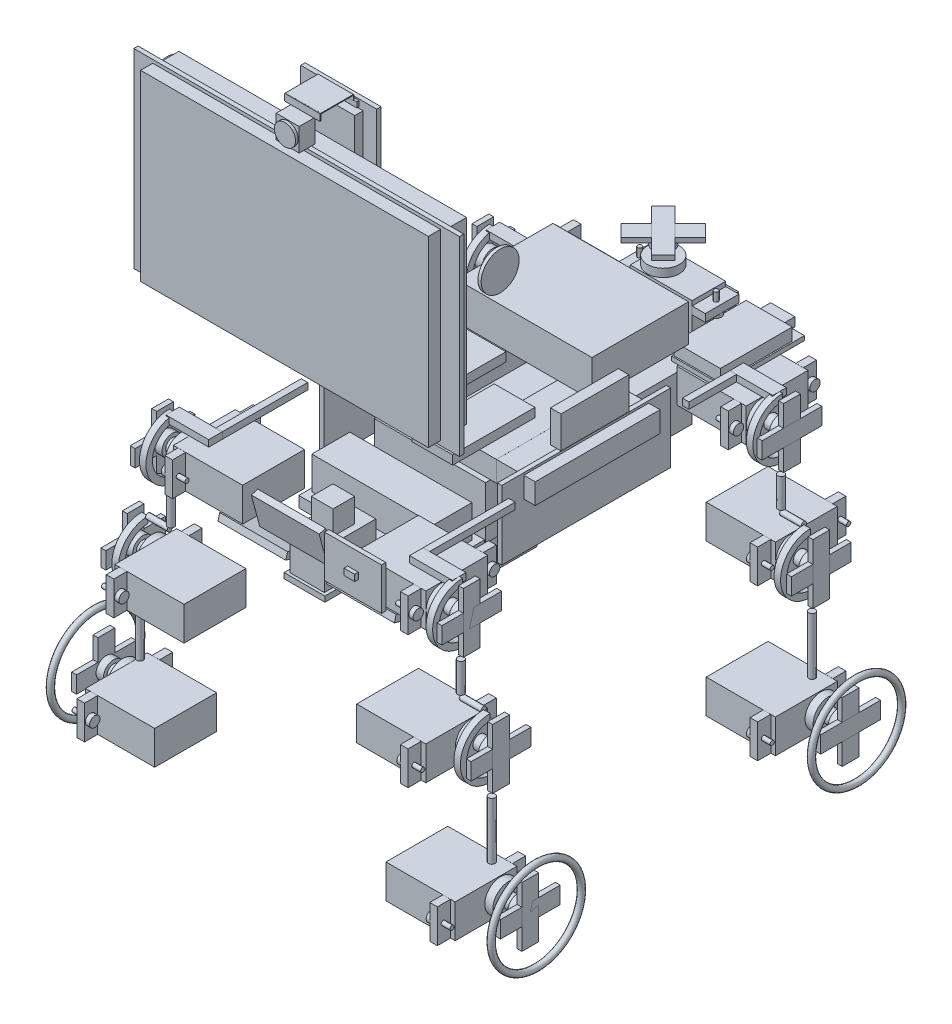
SolidWorks part; units mm, degrees
other "OV5640 camera - flex back"
other "OV5640 camera - flex up"
other "OV5640 camera - lens"
other "OV5640 camera - module"
other "ESP32-S3 CAM board - microSD (back)"
other "ESP32-S3 CAM board - camera connector"
other "ESP32-S3 CAM board - WROOM module"
other "ESP32-S3 CAM board - PCB"
other "Guition 4.3in screen - back parts"
other "Guition 4.3in screen - glass"
other "Guition 4.3in screen - PCB"
other "KCD1 switch - bezel"
other "Type-C 2S charging board - USB-C receptacle"
other "Type-C 2S charging board - parts"
other "Type-C 2S charging board - PCB"
other "Mini blade fuse holder"
other "2S 20A protection board"
other "2x18650 holder + 2x Samsung 35E"
other "Cavity speaker 3W"
other "MS3625 mic left"
other "MS3625 mic right"
other "Guition 4.3in screen - USB-C receptacle"
other "Ballast steel slug right"
other "Ballast steel slug left"
other "APDS-9960 gesture - chip"
other "APDS-9960 gesture - PCB"
other "OV5640 camera - flex down"
other "VL53L0X front obstacle laser"
other "VL53L0X rear desk-edge"
other "VL53L0X front desk-edge right"
other "VL53L0X front desk-edge left"
other "VL53L0X side laser left"
other "Servo plugs left"
other "PCA9685 solder tails left"
other "PCA9685 headers left"
other "PCA9685 servo board left"
other "VL53L0X side laser right"
other "Servo plugs right"
other "PCA9685 solder tails right"
other "PCA9685 headers right"
other "PCA9685 servo board right"
other "KCD1 switch - terminals"
other "KCD1 switch - body"
other "Hip BR - tab screw 2 M2x6"
other "Hip BR - tab screw 2 head"
other "Hip BR - tab screw 1 M2x6"
other "Hip BR - tab screw 1 head"
other "Hip BR - horn arms 2"
other "Hip BR - horn arms"
other "Hip BR - horn hub"
other "Hip BR - MG90S spline"
other "Hip BR - MG90S boss"
other "Hip BR - MG90S tab B"
other "Hip BR - MG90S tab A"
other "Hip BR - MG90S case"
other "Perfboard hub (2x Mini560, caps, resistors)"
other "MPR121 touch"
other "MPU6050 IMU"
other "VL53L0X rear obstacle laser"
other "Wheel BR (360) - MG90S boss"
other "Wheel BR (360) - MG90S tab B"
other "Wheel BR (360) - MG90S tab A"
other "Wheel BR (360) - MG90S case"
other "Knee BR - tab screw 2 M2x6"
other "Knee BR - tab screw 2 head"
other "Knee BR - tab screw 1 M2x6"
other "Knee BR - tab screw 1 head"
other "Knee BR - horn arms 2"
other "Knee BR - horn arms"
other "Knee BR - horn hub"
other "Knee BR - MG90S spline"
other "Knee BR - MG90S boss"
other "Knee BR - MG90S tab B"
other "Knee BR - MG90S tab A"
other "Knee BR - MG90S case"
other "Lead BR - wheel + knee, along the tub wall"
other "Lead BR - wheel + knee, hip exit"
other "Lead BR - wheel + knee, hip coil"
other "Lead BR - wheel + knee, thigh channel"
other "Lead BR - wheel, thigh hole"
other "Lead BR - wheel, knee coil"
other "Lead BR - wheel, shin channel"
other "O-ring tyre BR - 26x2.4 NBR"
other "Wheel BR (360) - tab screw 2 M2x6"
other "Wheel BR (360) - tab screw 2 head"
other "Wheel BR (360) - tab screw 1 M2x6"
other "Wheel BR (360) - tab screw 1 head"
other "Wheel BR (360) - horn arms 2"
other "Wheel BR (360) - horn arms"
other "Wheel BR (360) - horn hub"
other "Wheel BR (360) - MG90S spline"
other "Knee FR - MG90S boss"
other "Knee FR - MG90S tab B"
other "Knee FR - MG90S tab A"
other "Knee FR - MG90S case"
other "Hip FR - tab screw 2 M2x6"
other "Hip FR - tab screw 2 head"
other "Hip FR - tab screw 1 M2x6"
other "Hip FR - tab screw 1 head"
other "Hip FR - horn arms 2"
other "Hip FR - horn arms"
other "Hip FR - horn hub"
other "Hip FR - MG90S spline"
other "Hip FR - MG90S boss"
other "Hip FR - MG90S tab B"
other "Hip FR - MG90S tab A"
other "Hip FR - MG90S case"
other "Wheel FR (360) - horn arms 2"
other "Wheel FR (360) - horn arms"
other "Wheel FR (360) - horn hub"
other "Wheel FR (360) - MG90S spline"
other "Wheel FR (360) - MG90S boss"
other "Wheel FR (360) - MG90S tab B"
other "Wheel FR (360) - MG90S tab A"
other "Wheel FR (360) - MG90S case"
other "Knee FR - tab screw 2 M2x6"
other "Knee FR - tab screw 2 head"
other "Knee FR - tab screw 1 M2x6"
other "Knee FR - tab screw 1 head"
other "Knee FR - horn arms 2"
other "Knee FR - horn arms"
other "Knee FR - horn hub"
other "Knee FR - MG90S spline"
other "Hip BL - MG90S boss"
other "Hip BL - MG90S tab B"
other "Hip BL - MG90S tab A"
other "Hip BL - MG90S case"
other "Lead FR - wheel + knee, along the tub wall"
other "Lead FR - wheel + knee, hip exit"
other "Lead FR - wheel + knee, hip coil"
other "Lead FR - wheel + knee, thigh channel"
other "Lead FR - wheel, thigh hole"
other "Lead FR - wheel, knee coil"
other "Lead FR - wheel, shin channel"
other "O-ring tyre FR - 26x2.4 NBR"
other "Wheel FR (360) - tab screw 2 M2x6"
other "Wheel FR (360) - tab screw 2 head"
other "Wheel FR (360) - tab screw 1 M2x6"
other "Wheel FR (360) - tab screw 1 head"
other "Knee BL - horn arms 2"
other "Knee BL - horn arms"
other "Knee BL - horn hub"
other "Knee BL - MG90S spline"
other "Knee BL - MG90S boss"
other "Knee BL - MG90S tab B"
other "Knee BL - MG90S tab A"
other "Knee BL - MG90S case"
other "Hip BL - tab screw 2 M2x6"
other "Hip BL - tab screw 2 head"
other "Hip BL - tab screw 1 M2x6"
other "Hip BL - tab screw 1 head"
other "Hip BL - horn arms 2"
other "Hip BL - horn arms"
other "Hip BL - horn hub"
other "Hip BL - MG90S spline"
other "Wheel BL (360) - tab screw 2 M2x6"
other "Wheel BL (360) - tab screw 2 head"
other "Wheel BL (360) - tab screw 1 M2x6"
other "Wheel BL (360) - tab screw 1 head"
other "Wheel BL (360) - horn arms 2"
other "Wheel BL (360) - horn arms"
other "Wheel BL (360) - horn hub"
other "Wheel BL (360) - MG90S spline"
other "Wheel BL (360) - MG90S boss"
other "Wheel BL (360) - MG90S tab B"
other "Wheel BL (360) - MG90S tab A"
other "Wheel BL (360) - MG90S case"
other "Knee BL - tab screw 2 M2x6"
other "Knee BL - tab screw 2 head"
other "Knee BL - tab screw 1 M2x6"
other "Knee BL - tab screw 1 head"
other "Hip FL - horn arms 2"
other "Hip FL - horn arms"
other "Hip FL - horn hub"
other "Hip FL - MG90S spline"
other "Hip FL - MG90S boss"
other "Hip FL - MG90S tab B"
other "Hip FL - MG90S tab A"
other "Hip FL - MG90S case"
other "Lead BL - wheel + knee, along the tub wall"
other "Lead BL - wheel + knee, hip exit"
other "Lead BL - wheel + knee, hip coil"
other "Lead BL - wheel + knee, thigh channel"
other "Lead BL - wheel, thigh hole"
other "Lead BL - wheel, knee coil"
other "Lead BL - wheel, shin channel"
other "O-ring tyre BL - 26x2.4 NBR"
other "Knee FL - tab screw 2 M2x6"
other "Knee FL - tab screw 2 head"
other "Knee FL - tab screw 1 M2x6"
other "Knee FL - tab screw 1 head"
other "Knee FL - horn arms 2"
other "Knee FL - horn arms"
other "Knee FL - horn hub"
other "Knee FL - MG90S spline"
other "Knee FL - MG90S boss"
other "Knee FL - MG90S tab B"
other "Knee FL - MG90S tab A"
other "Knee FL - MG90S case"
other "Hip FL - tab screw 2 M2x6"
other "Hip FL - tab screw 2 head"
other "Hip FL - tab screw 1 M2x6"
other "Hip FL - tab screw 1 head"
other "Lead FL - wheel, thigh hole"
other "Lead FL - wheel, knee coil"
other "Lead FL - wheel, shin channel"
other "O-ring tyre FL - 26x2.4 NBR"
other "Wheel FL (360) - tab screw 2 M2x6"
other "Wheel FL (360) - tab screw 2 head"
other "Wheel FL (360) - tab screw 1 M2x6"
other "Wheel FL (360) - tab screw 1 head"
other "Wheel FL (360) - horn arms 2"
other "Wheel FL (360) - horn arms"
other "Wheel FL (360) - horn hub"
other "Wheel FL (360) - MG90S spline"
other "Wheel FL (360) - MG90S boss"
other "Wheel FL (360) - MG90S tab B"
other "Wheel FL (360) - MG90S tab A"
other "Wheel FL (360) - MG90S case"
other "Tail - tab screw 2 M2x6"
other "Tail - tab screw 2 head"
other "Tail - tab screw 1 M2x6"
other "Tail - tab screw 1 head"
other "Tail - horn arms 2"
other "Tail - horn arms"
other "Tail - horn hub"
other "Tail - MG90S spline"
other "Tail - MG90S boss"
other "Tail - MG90S tab B"
other "Tail - MG90S tab A"
other "Tail - MG90S case"
other "Lead FL - wheel + knee, along the tub wall"
other "Lead FL - wheel + knee, hip exit"
other "Lead FL - wheel + knee, hip coil"
other "Lead FL - wheel + knee, thigh channel"
ref_plane "Front Plane" through (0, 0, 0) normal (0, 0, 1) x (1, 0, 0)
ref_plane "Top Plane" through (0, 0, 0) normal (0, 1, 0) x (1, 0, 0)
ref_plane "Right Plane" through (0, 0, 0) normal (1, 0, 0) x (0, 0, -1)
sketch "Sketch1" plane through (0, 0, 0) normal (0, 0, 1) x (1, 0, 0)
  line L1 (-60, 74.4) -> (60, 74.4)
  line L2 (-60, 74.4) -> (-60, 144.6)
  line L3 (-60, 144.6) -> (60, 144.6)
  line L4 (60, 74.4) -> (60, 144.6)
extrude "Guition 4.3in screen - PCB" add sketch "Sketch1" along normal blind 1.6 from offset 71.5 separate body
sketch "Sketch2" plane through (0, 0, 0) normal (0, 0, 1) x (1, 0, 0)
  line L1 (-53, 76) -> (53, 76)
  line L2 (-53, 76) -> (-53, 143.4)
  line L3 (-53, 143.4) -> (53, 143.4)
  line L4 (53, 76) -> (53, 143.4)
extrude "Guition 4.3in screen - glass" add sketch "Sketch2" along normal blind 4.49 from offset 73.11 separate body
sketch "Sketch3" plane through (0, 0, 0) normal (0, 0, 1) x (1, 0, 0)
  line L1 (-53, 76.4) -> (53, 76.4)
  line L2 (-53, 76.4) -> (-53, 142.4)
  line L3 (-53, 142.4) -> (53, 142.4)
  line L4 (53, 76.4) -> (53, 142.4)
extrude "Guition 4.3in screen - back parts" add sketch "Sketch3" along normal blind 7.99 from offset 63.5 separate body
sketch "Sketch4" plane through (0, 0, 0) normal (0, 0, 1) x (1, 0, 0)
  line L1 (-14, 97.5) -> (14, 97.5)
  line L2 (-14, 97.5) -> (-14, 154.5)
  line L3 (-14, 154.5) -> (14, 154.5)
  line L4 (14, 97.5) -> (14, 154.5)
extrude "ESP32-S3 CAM board - PCB" add sketch "Sketch4" along normal blind 1.6 from offset 56 separate body
sketch "Sketch5" plane through (0, 0, 0) normal (0, 0, 1) x (1, 0, 0)
  line L1 (-9, 129) -> (9, 129)
  line L2 (-9, 129) -> (-9, 151.5)
  line L3 (-9, 151.5) -> (9, 151.5)
  line L4 (9, 129) -> (9, 151.5)
extrude "ESP32-S3 CAM board - WROOM module" add sketch "Sketch5" along normal blind 3.09 from offset 57.61 separate body
sketch "Sketch6" plane through (0, 0, 0) normal (0, 0, 1) x (1, 0, 0)
  line L1 (-7.5, 152) -> (7.5, 152)
  line L2 (-7.5, 152) -> (-7.5, 154)
  line L3 (-7.5, 154) -> (7.5, 154)
  line L4 (7.5, 152) -> (7.5, 154)
extrude "ESP32-S3 CAM board - camera connector" add sketch "Sketch6" along normal blind 0.78 from offset 57.61 separate body
sketch "Sketch7" plane through (0, 0, 0) normal (0, 0, 1) x (1, 0, 0)
  line L1 (-8, 120) -> (6, 120)
  line L2 (-8, 120) -> (-8, 134)
  line L3 (-8, 134) -> (6, 134)
  line L4 (6, 120) -> (6, 134)
extrude "ESP32-S3 CAM board - microSD (back)" add sketch "Sketch7" along normal blind 1.89 from offset 54.1 separate body
sketch "Sketch8" plane through (0, 0, 0) normal (0, 0, 1) x (1, 0, 0)
  line L1 (-4.25, 145) -> (4.25, 145)
  line L2 (-4.25, 145) -> (-4.25, 153.5)
  line L3 (-4.25, 153.5) -> (4.25, 153.5)
  line L4 (4.25, 145) -> (4.25, 153.5)
extrude "OV5640 camera - module" add sketch "Sketch8" along normal blind 5.9 from offset 70.5 separate body
sketch "Sketch9" plane through (0, 0, 0) normal (0, 0, 1) x (1, 0, 0)
  circle A0 centre (0, 149.25) radius 3.9
extrude "OV5640 camera - lens" add sketch "Sketch9" along normal blind 0.99 from offset 76.41 separate body
sketch "Sketch10" plane through (0, 0, 0) normal (0, 0, 1) x (1, 0, 0)
  line L1 (-6.5, 153.51) -> (6.5, 153.51)
  line L2 (-6.5, 153.51) -> (-6.5, 156)
  line L3 (-6.5, 156) -> (6.5, 156)
  line L4 (6.5, 153.51) -> (6.5, 156)
extrude "OV5640 camera - flex up" add sketch "Sketch10" along normal blind 0.3 from offset 70.7 separate body
sketch "Sketch11" plane through (0, 0, 0) normal (0, 0, 1) x (1, 0, 0)
  line L1 (-6.5, 155.7) -> (6.5, 155.7)
  line L2 (-6.5, 155.7) -> (-6.5, 156)
  line L3 (-6.5, 156) -> (6.5, 156)
  line L4 (6.5, 155.7) -> (6.5, 156)
extrude "OV5640 camera - flex back" add sketch "Sketch11" along normal blind 11.99 from offset 58.7 separate body
sketch "Sketch12" plane through (0, 0, 0) normal (0, 0, 1) x (1, 0, 0)
  line L1 (-6.5, 154.01) -> (6.5, 154.01)
  line L2 (-6.5, 154.01) -> (-6.5, 155.69)
  line L3 (-6.5, 155.69) -> (6.5, 155.69)
  line L4 (6.5, 154.01) -> (6.5, 155.69)
extrude "OV5640 camera - flex down" add sketch "Sketch12" along normal blind 0.3 from offset 58.4 separate body
sketch "Sketch13" plane through (0, 0, 0) normal (0, 0, 1) x (1, 0, 0)
  line L1 (13.6, 13.3) -> (34.6, 13.3)
  line L2 (13.6, 13.3) -> (13.6, 28.8)
  line L3 (13.6, 28.8) -> (34.6, 28.8)
  line L4 (34.6, 13.3) -> (34.6, 28.8)
extrude "APDS-9960 gesture - PCB" add sketch "Sketch13" along normal blind 1.6 from offset 74.85 separate body
sketch "Sketch14" plane through (0, 0, 0) normal (0, 0, 1) x (1, 0, 0)
  line L1 (22.13, 19.87) -> (26.07, 19.87)
  line L2 (22.13, 19.87) -> (22.13, 22.23)
  line L3 (22.13, 22.23) -> (26.07, 22.23)
  line L4 (26.07, 19.87) -> (26.07, 22.23)
extrude "APDS-9960 gesture - chip" add sketch "Sketch14" along normal blind 1.33 from offset 76.46 separate body
sketch "Sketch15" plane through (0, 0, 0) normal (0, 0, 1) x (1, 0, 0)
  line L1 (14.8, 2.45) -> (38.8, 2.45)
  line L2 (14.8, 2.45) -> (14.8, 9.95)
  line L3 (14.8, 9.95) -> (38.8, 9.95)
  line L4 (38.8, 2.45) -> (38.8, 9.95)
extrude "Ballast steel slug left" add sketch "Sketch15" along normal blind 15.8 from offset 71.9 separate body offset against normal yes
sketch "Sketch16" plane through (0, 0, 0) normal (0, 0, 1) x (1, 0, 0)
  line L1 (-38.8, 2.45) -> (-14.8, 2.45)
  line L2 (-38.8, 2.45) -> (-38.8, 9.95)
  line L3 (-38.8, 9.95) -> (-14.8, 9.95)
  line L4 (-14.8, 2.45) -> (-14.8, 9.95)
extrude "Ballast steel slug right" add sketch "Sketch16" along normal blind 15.8 from offset 71.9 separate body offset against normal yes
sketch "Sketch17" plane through (0, 0, 0) normal (0, 0, 1) x (1, 0, 0)
  line L1 (-60, 110.03) -> (-52.65, 110.03)
  line L2 (-60, 110.03) -> (-60, 118.97)
  line L3 (-60, 118.97) -> (-52.65, 118.97)
  line L4 (-52.65, 110.03) -> (-52.65, 118.97)
extrude "Guition 4.3in screen - USB-C receptacle" add sketch "Sketch17" along normal blind 3.19 from offset 68.3 separate body
sketch "Sketch18" plane through (0, 0, 0) normal (1, 0, 0) x (0, 0, -1)
  circle A0 centre (-59.5, 127.5) radius 7
extrude "MS3625 mic right" add sketch "Sketch18" along normal blind 1.19 from offset 61.39 separate body offset against normal yes
sketch "Sketch19" plane through (0, 0, 0) normal (1, 0, 0) x (0, 0, -1)
  circle A0 centre (-59.5, 127.5) radius 7
extrude "MS3625 mic left" add sketch "Sketch19" along normal blind 1.19 from offset 60.2 separate body
sketch "Sketch20" plane through (0, 0, 0) normal (0, 0, 1) x (1, 0, 0)
  line L1 (-14, 80) -> (14, 80)
  line L2 (-14, 80) -> (-14, 111)
  line L3 (-14, 111) -> (14, 111)
  line L4 (14, 80) -> (14, 111)
extrude "Cavity speaker 3W" add sketch "Sketch20" along normal blind 14.9 from offset 37.7 separate body
sketch "Sketch21" plane through (0, 0, 0) normal (0, 0, 1) x (1, 0, 0)
  line L1 (-20.5, 2.4) -> (20.5, 2.4)
  line L2 (-20.5, 2.4) -> (-20.5, 21.75)
  line L3 (-20.5, 21.75) -> (20.5, 21.75)
  line L4 (20.5, 2.4) -> (20.5, 21.75)
extrude "2x18650 holder + 2x Samsung 35E" add sketch "Sketch21" along normal blind 76 from offset 52 separate body offset against normal yes
sketch "Sketch22" plane through (0, 0, 0) normal (0, 0, 1) x (1, 0, 0)
  line L1 (-24.2, 3.4) -> (24.2, 3.4)
  line L2 (-24.2, 3.4) -> (-24.2, 7.4)
  line L3 (-24.2, 7.4) -> (24.2, 7.4)
  line L4 (24.2, 3.4) -> (24.2, 7.4)
extrude "2S 20A protection board" add sketch "Sketch22" along normal blind 20.1 from offset 28 separate body
sketch "Sketch23" plane through (0, 0, 0) normal (0, 0, 1) x (1, 0, 0)
  line L1 (-22.5, 7.9) -> (22.5, 7.9)
  line L2 (-22.5, 7.9) -> (-22.5, 19.9)
  line L3 (-22.5, 19.9) -> (22.5, 19.9)
  line L4 (22.5, 7.9) -> (22.5, 19.9)
extrude "Mini blade fuse holder" add sketch "Sketch23" along normal blind 14 from offset 31 separate body
sketch "Sketch24" plane through (0, 0, 0) normal (0, 0, 1) x (1, 0, 0)
  line L1 (18.5, 24.35) -> (36.5, 24.35)
  line L2 (18.5, 24.35) -> (18.5, 25.95)
  line L3 (18.5, 25.95) -> (36.5, 25.95)
  line L4 (36.5, 24.35) -> (36.5, 25.95)
extrude "Type-C 2S charging board - PCB" add sketch "Sketch24" along normal blind 31 from offset 77.5 separate body offset against normal yes
sketch "Sketch25" plane through (0, 0, 0) normal (0, 0, 1) x (1, 0, 0)
  line L1 (19, 25.96) -> (36, 25.96)
  line L2 (19, 25.96) -> (19, 30.45)
  line L3 (19, 30.45) -> (36, 30.45)
  line L4 (36, 25.96) -> (36, 30.45)
extrude "Type-C 2S charging board - parts" add sketch "Sketch25" along normal blind 26.5 from offset 73.5 separate body offset against normal yes
sketch "Sketch26" plane through (0, 0, 0) normal (0, 0, 1) x (1, 0, 0)
  line L1 (23.03, 25.95) -> (31.97, 25.95)
  line L2 (23.03, 25.95) -> (23.03, 29.21)
  line L3 (23.03, 29.21) -> (31.97, 29.21)
  line L4 (31.97, 25.95) -> (31.97, 29.21)
extrude "Type-C 2S charging board - USB-C receptacle" add sketch "Sketch26" along normal blind 7.35 from offset 78.5 separate body offset against normal yes
sketch "Sketch27" plane through (0, 0, 0) normal (0, 0, 1) x (1, 0, 0)
  line L1 (-7.5, 0.2) -> (7.5, 0.2)
  line L2 (-7.5, 0.2) -> (-7.5, 2.2)
  line L3 (-7.5, 2.2) -> (7.5, 2.2)
  line L4 (7.5, 0.2) -> (7.5, 2.2)
extrude "KCD1 switch - bezel" add sketch "Sketch27" along normal blind 21 from offset 49.2 separate body
sketch "Sketch28" plane through (0, 0, 0) normal (0, 0, 1) x (1, 0, 0)
  line L1 (-6.3, 2.21) -> (6.3, 2.21)
  line L2 (-6.3, 2.21) -> (-6.3, 16.2)
  line L3 (-6.3, 16.2) -> (6.3, 16.2)
  line L4 (6.3, 2.21) -> (6.3, 16.2)
extrude "KCD1 switch - body" add sketch "Sketch28" along normal blind 19 from offset 50.2 separate body
sketch "Sketch29" plane through (0, 0, 0) normal (0, 0, 1) x (1, 0, 0)
  line L1 (-4, 16.21) -> (4, 16.21)
  line L2 (-4, 16.21) -> (-4, 25)
  line L3 (-4, 25) -> (4, 25)
  line L4 (4, 16.21) -> (4, 25)
extrude "KCD1 switch - terminals" add sketch "Sketch29" along normal blind 8 from offset 55.7 separate body
sketch "Sketch30" plane through (0, 0, 0) normal (0, 0, 1) x (1, 0, 0)
  line L1 (-33.6, 5.6) -> (-32, 5.6)
  line L2 (-33.6, 5.6) -> (-33.6, 31)
  line L3 (-33.6, 31) -> (-32, 31)
  line L4 (-32, 5.6) -> (-32, 31)
extrude "PCA9685 servo board right" add sketch "Sketch30" along normal blind 62.2 from offset 31.1 separate body offset against normal yes
sketch "Sketch31" plane through (0, 0, 0) normal (0, 0, 1) x (1, 0, 0)
  line L1 (-31.99, 22.6) -> (-23.5, 22.6)
  line L2 (-31.99, 22.6) -> (-31.99, 30.2)
  line L3 (-31.99, 30.2) -> (-23.5, 30.2)
  line L4 (-23.5, 22.6) -> (-23.5, 30.2)
extrude "PCA9685 headers right" add sketch "Sketch31" along normal blind 46 from offset 23 separate body offset against normal yes
sketch "Sketch32" plane through (0, 0, 0) normal (0, 0, 1) x (1, 0, 0)
  line L1 (-37.8, 22.6) -> (-33.61, 22.6)
  line L2 (-37.8, 22.6) -> (-37.8, 30.2)
  line L3 (-37.8, 30.2) -> (-33.61, 30.2)
  line L4 (-33.61, 22.6) -> (-33.61, 30.2)
extrude "PCA9685 solder tails right" add sketch "Sketch32" along normal blind 46 from offset 23 separate body offset against normal yes
sketch "Sketch33" plane through (0, 0, 0) normal (0, 0, 1) x (1, 0, 0)
  line L1 (-23.49, 22.6) -> (-9.5, 22.6)
  line L2 (-23.49, 22.6) -> (-23.49, 30.2)
  line L3 (-23.49, 30.2) -> (-9.5, 30.2)
  line L4 (-9.5, 22.6) -> (-9.5, 30.2)
extrude "Servo plugs right" add sketch "Sketch33" along normal blind 46 from offset 23 separate body offset against normal yes
sketch "Sketch34" plane through (0, 0, 0) normal (0, 0, 1) x (1, 0, 0)
  line L1 (-36.8, 34.3) -> (-32.9, 34.3)
  line L2 (-36.8, 34.3) -> (-36.8, 46.1)
  line L3 (-36.8, 46.1) -> (-32.9, 46.1)
  line L4 (-32.9, 34.3) -> (-32.9, 46.1)
extrude "VL53L0X side laser right" add sketch "Sketch34" along normal blind 25 from offset 12.5 separate body offset against normal yes
sketch "Sketch35" plane through (0, 0, 0) normal (0, 0, 1) x (1, 0, 0)
  line L1 (32, 5.6) -> (33.6, 5.6)
  line L2 (32, 5.6) -> (32, 31)
  line L3 (32, 31) -> (33.6, 31)
  line L4 (33.6, 5.6) -> (33.6, 31)
extrude "PCA9685 servo board left" add sketch "Sketch35" along normal blind 62.2 from offset 31.1 separate body offset against normal yes
sketch "Sketch36" plane through (0, 0, 0) normal (0, 0, 1) x (1, 0, 0)
  line L1 (23.5, 22.6) -> (31.99, 22.6)
  line L2 (23.5, 22.6) -> (23.5, 30.2)
  line L3 (23.5, 30.2) -> (31.99, 30.2)
  line L4 (31.99, 22.6) -> (31.99, 30.2)
extrude "PCA9685 headers left" add sketch "Sketch36" along normal blind 46 from offset 23 separate body offset against normal yes
sketch "Sketch37" plane through (0, 0, 0) normal (0, 0, 1) x (1, 0, 0)
  line L1 (33.61, 22.6) -> (37.8, 22.6)
  line L2 (33.61, 22.6) -> (33.61, 30.2)
  line L3 (33.61, 30.2) -> (37.8, 30.2)
  line L4 (37.8, 22.6) -> (37.8, 30.2)
extrude "PCA9685 solder tails left" add sketch "Sketch37" along normal blind 46 from offset 23 separate body offset against normal yes
sketch "Sketch38" plane through (0, 0, 0) normal (0, 0, 1) x (1, 0, 0)
  line L1 (9.5, 22.6) -> (23.49, 22.6)
  line L2 (9.5, 22.6) -> (9.5, 30.2)
  line L3 (9.5, 30.2) -> (23.49, 30.2)
  line L4 (23.49, 22.6) -> (23.49, 30.2)
extrude "Servo plugs left" add sketch "Sketch38" along normal blind 46 from offset 23 separate body offset against normal yes
sketch "Sketch39" plane through (0, 0, 0) normal (0, 0, 1) x (1, 0, 0)
  line L1 (32.9, 34.3) -> (36.8, 34.3)
  line L2 (32.9, 34.3) -> (32.9, 46.1)
  line L3 (32.9, 46.1) -> (36.8, 46.1)
  line L4 (36.8, 34.3) -> (36.8, 46.1)
extrude "VL53L0X side laser left" add sketch "Sketch39" along normal blind 25 from offset 12.5 separate body offset against normal yes
sketch "Sketch40" plane through (0, 0, 0) normal (1, 0, 0) x (0, 0, -1)
  line L0 (-58, 2.7) -> (-69.5911, 5.8058)
  line L1 (-69.5911, 5.8058) -> (-68.9441, 8.2206)
  line L2 (-68.9441, 8.2206) -> (-57.353, 5.1148)
  line L3 (-57.353, 5.1148) -> (-58, 2.7)
extrude "VL53L0X front desk-edge left" add sketch "Sketch40" along normal blind 24.98 from offset 7.51 separate body
sketch "Sketch41" plane through (0, 0, 0) normal (1, 0, 0) x (0, 0, -1)
  line L0 (-58, 2.7) -> (-69.5911, 5.8058)
  line L1 (-69.5911, 5.8058) -> (-68.9441, 8.2206)
  line L2 (-68.9441, 8.2206) -> (-57.353, 5.1148)
  line L3 (-57.353, 5.1148) -> (-58, 2.7)
extrude "VL53L0X front desk-edge right" add sketch "Sketch41" along normal blind 24.98 from offset 32.49 separate body offset against normal yes
sketch "Sketch42" plane through (0, 0, 0) normal (1, 0, 0) x (0, 0, -1)
  line L0 (58, 2.7) -> (69.5911, 5.8058)
  line L1 (69.5911, 5.8058) -> (68.9441, 8.2206)
  line L2 (68.9441, 8.2206) -> (57.353, 5.1148)
  line L3 (57.353, 5.1148) -> (58, 2.7)
extrude "VL53L0X rear desk-edge" add sketch "Sketch42" along normal blind 24.98 from offset 12.49 separate body offset against normal yes
sketch "Sketch43" plane through (0, 0, 0) normal (1, 0, 0) x (0, 0, -1)
  line L0 (-74.19, 16.4) -> (-77.3, 28)
  line L1 (-77.3, 28) -> (-74.8852, 28.647)
  line L2 (-74.8852, 28.647) -> (-71.7752, 17.047)
  line L3 (-71.7752, 17.047) -> (-74.19, 16.4)
extrude "VL53L0X front obstacle laser" add sketch "Sketch43" along normal blind 25 from offset 12.5 separate body offset against normal yes
sketch "Sketch44" plane through (0, 0, 0) normal (1, 0, 0) x (0, 0, -1)
  line L0 (74.19, 16.4) -> (77.3, 28)
  line L1 (77.3, 28) -> (74.8852, 28.647)
  line L2 (74.8852, 28.647) -> (71.7752, 17.047)
  line L3 (71.7752, 17.047) -> (74.19, 16.4)
extrude "VL53L0X rear obstacle laser" add sketch "Sketch44" along normal blind 25 from offset 12.5 separate body offset against normal yes
sketch "Sketch45" plane through (0, 0, 0) normal (0, 0, 1) x (1, 0, 0)
  line L1 (-8.2, 44.2) -> (8.2, 44.2)
  line L2 (-8.2, 44.2) -> (-8.2, 47.5)
  line L3 (-8.2, 47.5) -> (8.2, 47.5)
  line L4 (8.2, 44.2) -> (8.2, 47.5)
extrude "MPU6050 IMU" add sketch "Sketch45" along normal blind 21.2 from offset 4.2 separate body
sketch "Sketch46" plane through (0, 0, 0) normal (0, 0, 1) x (1, 0, 0)
  line L1 (16.3, 44.2) -> (31.3, 44.2)
  line L2 (16.3, 44.2) -> (16.3, 47.5)
  line L3 (16.3, 47.5) -> (31.3, 47.5)
  line L4 (31.3, 44.2) -> (31.3, 47.5)
extrude "MPR121 touch" add sketch "Sketch46" along normal blind 30.3 from offset 16.6 separate body
sketch "Sketch47" plane through (0, 0, 0) normal (0, 0, 1) x (1, 0, 0)
  line L1 (-25, 33) -> (25, 33)
  line L2 (-25, 33) -> (-25, 46.6)
  line L3 (-25, 46.6) -> (25, 46.6)
  line L4 (25, 33) -> (25, 46.6)
extrude "Perfboard hub (2x Mini560, caps, resistors)" add sketch "Sketch47" along normal blind 35.6 from offset 46.3 separate body offset against normal yes
sketch "Sketch48" plane through (0, 0, 0) normal (0, 0, 1) x (1, 0, 0)
  line L1 (-46.5, 11.8) -> (-21, 11.8)
  line L2 (-46.5, 11.8) -> (-46.5, 24.2)
  line L3 (-46.5, 24.2) -> (-21, 24.2)
  line L4 (-21, 11.8) -> (-21, 24.2)
extrude "Hip BR - MG90S case" add sketch "Sketch48" along normal blind 22.8 from offset 68.8 separate body offset against normal yes
sketch "Sketch49" plane through (0, 0, 0) normal (0, 0, 1) x (1, 0, 0)
  line L1 (-44.8, 11.8) -> (-42, 11.8)
  line L2 (-44.8, 11.8) -> (-44.8, 24.2)
  line L3 (-44.8, 24.2) -> (-42, 24.2)
  line L4 (-42, 11.8) -> (-42, 24.2)
extrude "Hip BR - MG90S tab A" add sketch "Sketch49" along normal blind 4.84 from offset 73.65 separate body offset against normal yes
sketch "Sketch50" plane through (0, 0, 0) normal (0, 0, 1) x (1, 0, 0)
  line L1 (-44.8, 11.8) -> (-42, 11.8)
  line L2 (-44.8, 11.8) -> (-44.8, 24.2)
  line L3 (-44.8, 24.2) -> (-42, 24.2)
  line L4 (-42, 11.8) -> (-42, 24.2)
extrude "Hip BR - MG90S tab B" add sketch "Sketch50" along normal blind 4.84 from offset 45.99 separate body offset against normal yes
sketch "Sketch51" plane through (0, 0, 0) normal (1, 0, 0) x (0, 0, -1)
  circle A0 centre (52, 18) radius 5.9
extrude "Hip BR - MG90S boss" add sketch "Sketch51" along normal blind 2.99 from offset 49.5 separate body offset against normal yes
sketch "Sketch52" plane through (0, 0, 0) normal (1, 0, 0) x (0, 0, -1)
  circle A0 centre (52, 18) radius 2.45
extrude "Hip BR - MG90S spline" add sketch "Sketch52" along normal blind 6.89 from offset 56.4 separate body offset against normal yes
sketch "Sketch53" plane through (0, 0, 0) normal (1, 0, 0) x (0, 0, -1)
  circle A0 centre (52, 18) radius 3.8
extrude "Hip BR - horn hub" add sketch "Sketch53" along normal blind 2.69 from offset 55.59 separate body offset against normal yes
sketch "Sketch54" plane through (0, 0, 0) normal (0, 0, 1) x (1, 0, 0)
  line L1 (-57.4, 7) -> (-55.6, 7)
  line L2 (-57.4, 7) -> (-57.4, 29)
  line L3 (-57.4, 29) -> (-55.6, 29)
  line L4 (-55.6, 7) -> (-55.6, 29)
extrude "Hip BR - horn arms" add sketch "Sketch54" along normal blind 6.2 from offset 55.1 separate body offset against normal yes
sketch "Sketch55" plane through (0, 0, 0) normal (0, 0, 1) x (1, 0, 0)
  line L1 (-57.4, 14.9) -> (-55.6, 14.9)
  line L2 (-57.4, 14.9) -> (-57.4, 21.1)
  line L3 (-57.4, 21.1) -> (-55.6, 21.1)
  line L4 (-55.6, 14.9) -> (-55.6, 21.1)
extrude "Hip BR - horn arms 2" add sketch "Sketch55" along normal blind 22 from offset 63 separate body offset against normal yes
sketch "Sketch56" plane through (0, 0, 0) normal (1, 0, 0) x (0, 0, -1)
  circle A0 centre (71.475, 18) radius 1.9
extrude "Hip BR - tab screw 1 head" add sketch "Sketch56" along normal blind 1.59 from offset 46.4 separate body offset against normal yes
sketch "Sketch57" plane through (0, 0, 0) normal (1, 0, 0) x (0, 0, -1)
  circle A0 centre (71.475, 18) radius 0.8
extrude "Hip BR - tab screw 1 M2x6" add sketch "Sketch57" along normal blind 6 from offset 44.8 separate body offset against normal yes
sketch "Sketch58" plane through (0, 0, 0) normal (1, 0, 0) x (0, 0, -1)
  circle A0 centre (43.325, 18) radius 1.9
extrude "Hip BR - tab screw 2 head" add sketch "Sketch58" along normal blind 1.59 from offset 46.4 separate body offset against normal yes
sketch "Sketch59" plane through (0, 0, 0) normal (1, 0, 0) x (0, 0, -1)
  circle A0 centre (43.325, 18) radius 0.8
extrude "Hip BR - tab screw 2 M2x6" add sketch "Sketch59" along normal blind 6 from offset 44.8 separate body offset against normal yes
sketch "Sketch60" plane through (0, 0, 0) normal (0, 0, 1) x (1, 0, 0)
  line L1 (-57.3, -26.2) -> (-31.8, -26.2)
  line L2 (-57.3, -26.2) -> (-57.3, -13.8)
  line L3 (-57.3, -13.8) -> (-31.8, -13.8)
  line L4 (-31.8, -26.2) -> (-31.8, -13.8)
extrude "Knee BR - MG90S case" add sketch "Sketch60" along normal blind 22.8 from offset 68.8 separate body offset against normal yes
sketch "Sketch61" plane through (0, 0, 0) normal (0, 0, 1) x (1, 0, 0)
  line L1 (-55.6, -26.2) -> (-52.8, -26.2)
  line L2 (-55.6, -26.2) -> (-55.6, -13.8)
  line L3 (-55.6, -13.8) -> (-52.8, -13.8)
  line L4 (-52.8, -26.2) -> (-52.8, -13.8)
extrude "Knee BR - MG90S tab A" add sketch "Sketch61" along normal blind 4.84 from offset 73.65 separate body offset against normal yes
sketch "Sketch62" plane through (0, 0, 0) normal (0, 0, 1) x (1, 0, 0)
  line L1 (-55.6, -26.2) -> (-52.8, -26.2)
  line L2 (-55.6, -26.2) -> (-55.6, -13.8)
  line L3 (-55.6, -13.8) -> (-52.8, -13.8)
  line L4 (-52.8, -26.2) -> (-52.8, -13.8)
extrude "Knee BR - MG90S tab B" add sketch "Sketch62" along normal blind 4.84 from offset 45.99 separate body offset against normal yes
sketch "Sketch63" plane through (0, 0, 0) normal (1, 0, 0) x (0, 0, -1)
  circle A0 centre (52, -20) radius 5.9
extrude "Knee BR - MG90S boss" add sketch "Sketch63" along normal blind 2.99 from offset 60.3 separate body offset against normal yes
sketch "Sketch64" plane through (0, 0, 0) normal (1, 0, 0) x (0, 0, -1)
  circle A0 centre (52, -20) radius 2.45
extrude "Knee BR - MG90S spline" add sketch "Sketch64" along normal blind 6.89 from offset 67.2 separate body offset against normal yes
sketch "Sketch65" plane through (0, 0, 0) normal (1, 0, 0) x (0, 0, -1)
  circle A0 centre (52, -20) radius 3.8
extrude "Knee BR - horn hub" add sketch "Sketch65" along normal blind 2.69 from offset 66.39 separate body offset against normal yes
sketch "Sketch66" plane through (0, 0, 0) normal (0, 0, 1) x (1, 0, 0)
  line L1 (-68.2, -31) -> (-66.4, -31)
  line L2 (-68.2, -31) -> (-68.2, -9)
  line L3 (-68.2, -9) -> (-66.4, -9)
  line L4 (-66.4, -31) -> (-66.4, -9)
extrude "Knee BR - horn arms" add sketch "Sketch66" along normal blind 6.2 from offset 55.1 separate body offset against normal yes
sketch "Sketch67" plane through (0, 0, 0) normal (0, 0, 1) x (1, 0, 0)
  line L1 (-68.2, -23.1) -> (-66.4, -23.1)
  line L2 (-68.2, -23.1) -> (-68.2, -16.9)
  line L3 (-68.2, -16.9) -> (-66.4, -16.9)
  line L4 (-66.4, -23.1) -> (-66.4, -16.9)
extrude "Knee BR - horn arms 2" add sketch "Sketch67" along normal blind 22 from offset 63 separate body offset against normal yes
sketch "Sketch68" plane through (0, 0, 0) normal (1, 0, 0) x (0, 0, -1)
  circle A0 centre (71.475, -20) radius 1.9
extrude "Knee BR - tab screw 1 head" add sketch "Sketch68" along normal blind 1.59 from offset 52.79 separate body offset against normal yes
sketch "Sketch69" plane through (0, 0, 0) normal (1, 0, 0) x (0, 0, -1)
  circle A0 centre (71.475, -20) radius 0.8
extrude "Knee BR - tab screw 1 M2x6" add sketch "Sketch69" along normal blind 6 from offset 58.8 separate body offset against normal yes
sketch "Sketch70" plane through (0, 0, 0) normal (1, 0, 0) x (0, 0, -1)
  circle A0 centre (43.325, -20) radius 1.9
extrude "Knee BR - tab screw 2 head" add sketch "Sketch70" along normal blind 1.59 from offset 52.79 separate body offset against normal yes
sketch "Sketch71" plane through (0, 0, 0) normal (1, 0, 0) x (0, 0, -1)
  circle A0 centre (43.325, -20) radius 0.8
extrude "Knee BR - tab screw 2 M2x6" add sketch "Sketch71" along normal blind 6 from offset 58.8 separate body offset against normal yes
sketch "Sketch72" plane through (0, 0, 0) normal (0, 0, 1) x (1, 0, 0)
  line L1 (-68.1, -71.2) -> (-42.6, -71.2)
  line L2 (-68.1, -71.2) -> (-68.1, -58.8)
  line L3 (-68.1, -58.8) -> (-42.6, -58.8)
  line L4 (-42.6, -71.2) -> (-42.6, -58.8)
extrude "Wheel BR (360) - MG90S case" add sketch "Sketch72" along normal blind 22.8 from offset 58 separate body offset against normal yes
sketch "Sketch73" plane through (0, 0, 0) normal (0, 0, 1) x (1, 0, 0)
  line L1 (-66.4, -71.2) -> (-63.6, -71.2)
  line L2 (-66.4, -71.2) -> (-66.4, -58.8)
  line L3 (-66.4, -58.8) -> (-63.6, -58.8)
  line L4 (-63.6, -71.2) -> (-63.6, -58.8)
extrude "Wheel BR (360) - MG90S tab A" add sketch "Sketch73" along normal blind 4.84 from offset 62.85 separate body offset against normal yes
sketch "Sketch74" plane through (0, 0, 0) normal (0, 0, 1) x (1, 0, 0)
  line L1 (-66.4, -71.2) -> (-63.6, -71.2)
  line L2 (-66.4, -71.2) -> (-66.4, -58.8)
  line L3 (-66.4, -58.8) -> (-63.6, -58.8)
  line L4 (-63.6, -71.2) -> (-63.6, -58.8)
extrude "Wheel BR (360) - MG90S tab B" add sketch "Sketch74" along normal blind 4.84 from offset 35.19 separate body offset against normal yes
sketch "Sketch75" plane through (0, 0, 0) normal (1, 0, 0) x (0, 0, -1)
  circle A0 centre (52, -65) radius 5.9
extrude "Wheel BR (360) - MG90S boss" add sketch "Sketch75" along normal blind 2.99 from offset 71.1 separate body offset against normal yes
sketch "Sketch76" plane through (0, 0, 0) normal (1, 0, 0) x (0, 0, -1)
  circle A0 centre (52, -65) radius 2.45
extrude "Wheel BR (360) - MG90S spline" add sketch "Sketch76" along normal blind 6.89 from offset 78 separate body offset against normal yes
sketch "Sketch77" plane through (0, 0, 0) normal (1, 0, 0) x (0, 0, -1)
  circle A0 centre (52, -65) radius 3.8
extrude "Wheel BR (360) - horn hub" add sketch "Sketch77" along normal blind 2.69 from offset 77.19 separate body offset against normal yes
sketch "Sketch78" plane through (0, 0, 0) normal (0, 0, 1) x (1, 0, 0)
  line L1 (-79, -76) -> (-77.2, -76)
  line L2 (-79, -76) -> (-79, -54)
  line L3 (-79, -54) -> (-77.2, -54)
  line L4 (-77.2, -76) -> (-77.2, -54)
extrude "Wheel BR (360) - horn arms" add sketch "Sketch78" along normal blind 6.2 from offset 55.1 separate body offset against normal yes
sketch "Sketch79" plane through (0, 0, 0) normal (0, 0, 1) x (1, 0, 0)
  line L1 (-79, -68.1) -> (-77.2, -68.1)
  line L2 (-79, -68.1) -> (-79, -61.9)
  line L3 (-79, -61.9) -> (-77.2, -61.9)
  line L4 (-77.2, -68.1) -> (-77.2, -61.9)
extrude "Wheel BR (360) - horn arms 2" add sketch "Sketch79" along normal blind 22 from offset 63 separate body offset against normal yes
sketch "Sketch80" plane through (0, 0, 0) normal (1, 0, 0) x (0, 0, -1)
  circle A0 centre (60.675, -65) radius 1.9
extrude "Wheel BR (360) - tab screw 1 head" add sketch "Sketch80" along normal blind 1.59 from offset 63.59 separate body offset against normal yes
sketch "Sketch81" plane through (0, 0, 0) normal (1, 0, 0) x (0, 0, -1)
  circle A0 centre (60.675, -65) radius 0.8
extrude "Wheel BR (360) - tab screw 1 M2x6" add sketch "Sketch81" along normal blind 6 from offset 69.6 separate body offset against normal yes
sketch "Sketch82" plane through (0, 0, 0) normal (1, 0, 0) x (0, 0, -1)
  circle A0 centre (32.525, -65) radius 1.9
extrude "Wheel BR (360) - tab screw 2 head" add sketch "Sketch82" along normal blind 1.59 from offset 63.59 separate body offset against normal yes
sketch "Sketch83" plane through (0, 0, 0) normal (1, 0, 0) x (0, 0, -1)
  circle A0 centre (32.525, -65) radius 0.8
extrude "Wheel BR (360) - tab screw 2 M2x6" add sketch "Sketch83" along normal blind 6 from offset 69.6 separate body offset against normal yes
ref_plane "Plane1" through (0, 0, -52) normal (0, 0, 1) x (1, 0, 0)
sketch "Sketch84" plane through (0, 0, -52) normal (0, 0, 1) x (1, 0, 0)
  line L0 (-87.268, -65) -> (-75.1, -65) construction
  circle A0 centre (-81.2, -48.38) radius 1.1
revolve "O-ring tyre BR - 26x2.4 NBR" add sketch "Sketch84" angle 360 about L0
sketch "Sketch85" plane through (0, 0, 0) normal (0, 1, 0) x (1, 0, 0)
  circle A0 centre (-64.8, 52) radius 1.2
extrude "Lead BR - wheel, shin channel" add sketch "Sketch85" along normal blind 21 from offset 56 separate body offset against normal yes
sketch "Sketch86" plane through (0, 0, 0) normal (1, 0, 0) x (0, 0, -1)
  line L0 (52, -9) -> (52, -11.4)
  line L1 (52, -28.6) -> (52, -31)
  arc A0 (52, -31) -> (52, -9) centre (52, -20) cw
  arc A1 (52, -11.4) -> (52, -28.6) centre (52, -20) ccw
extrude "Lead BR - wheel, knee coil" add sketch "Sketch86" along normal blind 2.4 from offset 64.2 separate body offset against normal yes
sketch "Sketch87" plane through (0, 0, 0) normal (1, 0, 0) x (0, 0, -1)
  circle A0 centre (52, -9) radius 1
extrude "Lead BR - wheel, thigh hole" add sketch "Sketch87" along normal blind 7.99 from offset 61.79 separate body offset against normal yes
sketch "Sketch88" plane through (0, 0, 0) normal (0, 1, 0) x (1, 0, 0)
  circle A0 centre (-53.4, 52) radius 1.2
extrude "Lead BR - wheel + knee, thigh channel" add sketch "Sketch88" along normal blind 10.8 from offset 7.8 separate body offset against normal yes
sketch "Sketch89" plane through (0, 0, 0) normal (1, 0, 0) x (0, 0, -1)
  line L0 (52, 29) -> (52, 26.6)
  line L1 (52, 9.4) -> (52, 7)
  arc A0 (52, 7) -> (52, 29) centre (52, 18) cw
  arc A1 (52, 26.6) -> (52, 9.4) centre (52, 18) ccw
extrude "Lead BR - wheel + knee, hip coil" add sketch "Sketch89" along normal blind 2.4 from offset 54 separate body offset against normal yes
sketch "Sketch90" plane through (0, 0, 0) normal (0, 0, 1) x (1, 0, 0)
  line L1 (-52.8, 26.6) -> (-37, 26.6)
  line L2 (-52.8, 26.6) -> (-52.8, 29)
  line L3 (-52.8, 29) -> (-37, 29)
  line L4 (-37, 26.6) -> (-37, 29)
extrude "Lead BR - wheel + knee, hip exit" add sketch "Sketch90" along normal blind 5 from offset 54.5 separate body offset against normal yes
sketch "Sketch91" plane through (0, 0, 0) normal (0, 0, 1) x (1, 0, 0)
  line L1 (-39.4, 26.6) -> (-37, 26.6)
  line L2 (-39.4, 26.6) -> (-39.4, 29)
  line L3 (-39.4, 29) -> (-37, 29)
  line L4 (-37, 26.6) -> (-37, 29)
extrude "Lead BR - wheel + knee, along the tub wall" add sketch "Sketch91" along normal blind 17.5 from offset 49.5 separate body offset against normal yes
sketch "Sketch92" plane through (0, 0, 0) normal (0, 0, 1) x (1, 0, 0)
  line L1 (-46.5, 11.8) -> (-21, 11.8)
  line L2 (-46.5, 11.8) -> (-46.5, 24.2)
  line L3 (-46.5, 24.2) -> (-21, 24.2)
  line L4 (-21, 11.8) -> (-21, 24.2)
extrude "Hip FR - MG90S case" add sketch "Sketch92" along normal blind 22.8 from offset 49.2 separate body
sketch "Sketch93" plane through (0, 0, 0) normal (0, 0, 1) x (1, 0, 0)
  line L1 (-44.8, 11.8) -> (-42, 11.8)
  line L2 (-44.8, 11.8) -> (-44.8, 24.2)
  line L3 (-44.8, 24.2) -> (-42, 24.2)
  line L4 (-42, 11.8) -> (-42, 24.2)
extrude "Hip FR - MG90S tab A" add sketch "Sketch93" along normal blind 4.84 from offset 44.35 separate body
sketch "Sketch94" plane through (0, 0, 0) normal (0, 0, 1) x (1, 0, 0)
  line L1 (-44.8, 11.8) -> (-42, 11.8)
  line L2 (-44.8, 11.8) -> (-44.8, 24.2)
  line L3 (-44.8, 24.2) -> (-42, 24.2)
  line L4 (-42, 11.8) -> (-42, 24.2)
extrude "Hip FR - MG90S tab B" add sketch "Sketch94" along normal blind 4.84 from offset 72.01 separate body
sketch "Sketch95" plane through (0, 0, 0) normal (1, 0, 0) x (0, 0, -1)
  circle A0 centre (-66, 18) radius 5.9
extrude "Hip FR - MG90S boss" add sketch "Sketch95" along normal blind 2.99 from offset 49.5 separate body offset against normal yes
sketch "Sketch96" plane through (0, 0, 0) normal (1, 0, 0) x (0, 0, -1)
  circle A0 centre (-66, 18) radius 2.45
extrude "Hip FR - MG90S spline" add sketch "Sketch96" along normal blind 6.89 from offset 56.4 separate body offset against normal yes
sketch "Sketch97" plane through (0, 0, 0) normal (1, 0, 0) x (0, 0, -1)
  circle A0 centre (-66, 18) radius 3.8
extrude "Hip FR - horn hub" add sketch "Sketch97" along normal blind 2.69 from offset 55.59 separate body offset against normal yes
sketch "Sketch98" plane through (0, 0, 0) normal (0, 0, 1) x (1, 0, 0)
  line L1 (-57.4, 7) -> (-55.6, 7)
  line L2 (-57.4, 7) -> (-57.4, 29)
  line L3 (-57.4, 29) -> (-55.6, 29)
  line L4 (-55.6, 7) -> (-55.6, 29)
extrude "Hip FR - horn arms" add sketch "Sketch98" along normal blind 6.2 from offset 62.9 separate body
sketch "Sketch99" plane through (0, 0, 0) normal (0, 0, 1) x (1, 0, 0)
  line L1 (-57.4, 14.9) -> (-55.6, 14.9)
  line L2 (-57.4, 14.9) -> (-57.4, 21.1)
  line L3 (-57.4, 21.1) -> (-55.6, 21.1)
  line L4 (-55.6, 14.9) -> (-55.6, 21.1)
extrude "Hip FR - horn arms 2" add sketch "Sketch99" along normal blind 22 from offset 55 separate body
sketch "Sketch100" plane through (0, 0, 0) normal (1, 0, 0) x (0, 0, -1)
  circle A0 centre (-46.525, 18) radius 1.9
extrude "Hip FR - tab screw 1 head" add sketch "Sketch100" along normal blind 1.59 from offset 46.4 separate body offset against normal yes
sketch "Sketch101" plane through (0, 0, 0) normal (1, 0, 0) x (0, 0, -1)
  circle A0 centre (-46.525, 18) radius 0.8
extrude "Hip FR - tab screw 1 M2x6" add sketch "Sketch101" along normal blind 6 from offset 44.8 separate body offset against normal yes
sketch "Sketch102" plane through (0, 0, 0) normal (1, 0, 0) x (0, 0, -1)
  circle A0 centre (-74.675, 18) radius 1.9
extrude "Hip FR - tab screw 2 head" add sketch "Sketch102" along normal blind 1.59 from offset 46.4 separate body offset against normal yes
sketch "Sketch103" plane through (0, 0, 0) normal (1, 0, 0) x (0, 0, -1)
  circle A0 centre (-74.675, 18) radius 0.8
extrude "Hip FR - tab screw 2 M2x6" add sketch "Sketch103" along normal blind 6 from offset 44.8 separate body offset against normal yes
sketch "Sketch104" plane through (0, 0, 0) normal (0, 0, 1) x (1, 0, 0)
  line L1 (-57.3, -26.2) -> (-31.8, -26.2)
  line L2 (-57.3, -26.2) -> (-57.3, -13.8)
  line L3 (-57.3, -13.8) -> (-31.8, -13.8)
  line L4 (-31.8, -26.2) -> (-31.8, -13.8)
extrude "Knee FR - MG90S case" add sketch "Sketch104" along normal blind 22.8 from offset 60 separate body
sketch "Sketch105" plane through (0, 0, 0) normal (0, 0, 1) x (1, 0, 0)
  line L1 (-55.6, -26.2) -> (-52.8, -26.2)
  line L2 (-55.6, -26.2) -> (-55.6, -13.8)
  line L3 (-55.6, -13.8) -> (-52.8, -13.8)
  line L4 (-52.8, -26.2) -> (-52.8, -13.8)
extrude "Knee FR - MG90S tab A" add sketch "Sketch105" along normal blind 4.84 from offset 55.15 separate body
sketch "Sketch106" plane through (0, 0, 0) normal (0, 0, 1) x (1, 0, 0)
  line L1 (-55.6, -26.2) -> (-52.8, -26.2)
  line L2 (-55.6, -26.2) -> (-55.6, -13.8)
  line L3 (-55.6, -13.8) -> (-52.8, -13.8)
  line L4 (-52.8, -26.2) -> (-52.8, -13.8)
extrude "Knee FR - MG90S tab B" add sketch "Sketch106" along normal blind 4.84 from offset 82.81 separate body
sketch "Sketch107" plane through (0, 0, 0) normal (1, 0, 0) x (0, 0, -1)
  circle A0 centre (-66, -20) radius 5.9
extrude "Knee FR - MG90S boss" add sketch "Sketch107" along normal blind 2.99 from offset 60.3 separate body offset against normal yes
sketch "Sketch108" plane through (0, 0, 0) normal (1, 0, 0) x (0, 0, -1)
  circle A0 centre (-66, -20) radius 2.45
extrude "Knee FR - MG90S spline" add sketch "Sketch108" along normal blind 6.89 from offset 67.2 separate body offset against normal yes
sketch "Sketch109" plane through (0, 0, 0) normal (1, 0, 0) x (0, 0, -1)
  circle A0 centre (-66, -20) radius 3.8
extrude "Knee FR - horn hub" add sketch "Sketch109" along normal blind 2.69 from offset 66.39 separate body offset against normal yes
sketch "Sketch110" plane through (0, 0, 0) normal (0, 0, 1) x (1, 0, 0)
  line L1 (-68.2, -31) -> (-66.4, -31)
  line L2 (-68.2, -31) -> (-68.2, -9)
  line L3 (-68.2, -9) -> (-66.4, -9)
  line L4 (-66.4, -31) -> (-66.4, -9)
extrude "Knee FR - horn arms" add sketch "Sketch110" along normal blind 6.2 from offset 62.9 separate body
sketch "Sketch111" plane through (0, 0, 0) normal (0, 0, 1) x (1, 0, 0)
  line L1 (-68.2, -23.1) -> (-66.4, -23.1)
  line L2 (-68.2, -23.1) -> (-68.2, -16.9)
  line L3 (-68.2, -16.9) -> (-66.4, -16.9)
  line L4 (-66.4, -23.1) -> (-66.4, -16.9)
extrude "Knee FR - horn arms 2" add sketch "Sketch111" along normal blind 22 from offset 55 separate body
sketch "Sketch112" plane through (0, 0, 0) normal (1, 0, 0) x (0, 0, -1)
  circle A0 centre (-57.325, -20) radius 1.9
extrude "Knee FR - tab screw 1 head" add sketch "Sketch112" along normal blind 1.59 from offset 52.79 separate body offset against normal yes
sketch "Sketch113" plane through (0, 0, 0) normal (1, 0, 0) x (0, 0, -1)
  circle A0 centre (-57.325, -20) radius 0.8
extrude "Knee FR - tab screw 1 M2x6" add sketch "Sketch113" along normal blind 6 from offset 58.8 separate body offset against normal yes
sketch "Sketch114" plane through (0, 0, 0) normal (1, 0, 0) x (0, 0, -1)
  circle A0 centre (-85.475, -20) radius 1.9
extrude "Knee FR - tab screw 2 head" add sketch "Sketch114" along normal blind 1.59 from offset 52.79 separate body offset against normal yes
sketch "Sketch115" plane through (0, 0, 0) normal (1, 0, 0) x (0, 0, -1)
  circle A0 centre (-85.475, -20) radius 0.8
extrude "Knee FR - tab screw 2 M2x6" add sketch "Sketch115" along normal blind 6 from offset 58.8 separate body offset against normal yes
sketch "Sketch116" plane through (0, 0, 0) normal (0, 0, 1) x (1, 0, 0)
  line L1 (-68.1, -71.2) -> (-42.6, -71.2)
  line L2 (-68.1, -71.2) -> (-68.1, -58.8)
  line L3 (-68.1, -58.8) -> (-42.6, -58.8)
  line L4 (-42.6, -71.2) -> (-42.6, -58.8)
extrude "Wheel FR (360) - MG90S case" add sketch "Sketch116" along normal blind 22.8 from offset 60 separate body
sketch "Sketch117" plane through (0, 0, 0) normal (0, 0, 1) x (1, 0, 0)
  line L1 (-66.4, -71.2) -> (-63.6, -71.2)
  line L2 (-66.4, -71.2) -> (-66.4, -58.8)
  line L3 (-66.4, -58.8) -> (-63.6, -58.8)
  line L4 (-63.6, -71.2) -> (-63.6, -58.8)
extrude "Wheel FR (360) - MG90S tab A" add sketch "Sketch117" along normal blind 4.84 from offset 55.15 separate body
sketch "Sketch118" plane through (0, 0, 0) normal (0, 0, 1) x (1, 0, 0)
  line L1 (-66.4, -71.2) -> (-63.6, -71.2)
  line L2 (-66.4, -71.2) -> (-66.4, -58.8)
  line L3 (-66.4, -58.8) -> (-63.6, -58.8)
  line L4 (-63.6, -71.2) -> (-63.6, -58.8)
extrude "Wheel FR (360) - MG90S tab B" add sketch "Sketch118" along normal blind 4.84 from offset 82.81 separate body
sketch "Sketch119" plane through (0, 0, 0) normal (1, 0, 0) x (0, 0, -1)
  circle A0 centre (-66, -65) radius 5.9
extrude "Wheel FR (360) - MG90S boss" add sketch "Sketch119" along normal blind 2.99 from offset 71.1 separate body offset against normal yes
sketch "Sketch120" plane through (0, 0, 0) normal (1, 0, 0) x (0, 0, -1)
  circle A0 centre (-66, -65) radius 2.45
extrude "Wheel FR (360) - MG90S spline" add sketch "Sketch120" along normal blind 6.89 from offset 78 separate body offset against normal yes
sketch "Sketch121" plane through (0, 0, 0) normal (1, 0, 0) x (0, 0, -1)
  circle A0 centre (-66, -65) radius 3.8
extrude "Wheel FR (360) - horn hub" add sketch "Sketch121" along normal blind 2.69 from offset 77.19 separate body offset against normal yes
sketch "Sketch122" plane through (0, 0, 0) normal (0, 0, 1) x (1, 0, 0)
  line L1 (-79, -76) -> (-77.2, -76)
  line L2 (-79, -76) -> (-79, -54)
  line L3 (-79, -54) -> (-77.2, -54)
  line L4 (-77.2, -76) -> (-77.2, -54)
extrude "Wheel FR (360) - horn arms" add sketch "Sketch122" along normal blind 6.2 from offset 62.9 separate body
sketch "Sketch123" plane through (0, 0, 0) normal (0, 0, 1) x (1, 0, 0)
  line L1 (-79, -68.1) -> (-77.2, -68.1)
  line L2 (-79, -68.1) -> (-79, -61.9)
  line L3 (-79, -61.9) -> (-77.2, -61.9)
  line L4 (-77.2, -68.1) -> (-77.2, -61.9)
extrude "Wheel FR (360) - horn arms 2" add sketch "Sketch123" along normal blind 22 from offset 55 separate body
sketch "Sketch124" plane through (0, 0, 0) normal (1, 0, 0) x (0, 0, -1)
  circle A0 centre (-57.325, -65) radius 1.9
extrude "Wheel FR (360) - tab screw 1 head" add sketch "Sketch124" along normal blind 1.59 from offset 63.59 separate body offset against normal yes
sketch "Sketch125" plane through (0, 0, 0) normal (1, 0, 0) x (0, 0, -1)
  circle A0 centre (-57.325, -65) radius 0.8
extrude "Wheel FR (360) - tab screw 1 M2x6" add sketch "Sketch125" along normal blind 6 from offset 69.6 separate body offset against normal yes
sketch "Sketch126" plane through (0, 0, 0) normal (1, 0, 0) x (0, 0, -1)
  circle A0 centre (-85.475, -65) radius 1.9
extrude "Wheel FR (360) - tab screw 2 head" add sketch "Sketch126" along normal blind 1.59 from offset 63.59 separate body offset against normal yes
sketch "Sketch127" plane through (0, 0, 0) normal (1, 0, 0) x (0, 0, -1)
  circle A0 centre (-85.475, -65) radius 0.8
extrude "Wheel FR (360) - tab screw 2 M2x6" add sketch "Sketch127" along normal blind 6 from offset 69.6 separate body offset against normal yes
ref_plane "Plane2" through (0, 0, 66) normal (0, 0, 1) x (1, 0, 0)
sketch "Sketch128" plane through (0, 0, 66) normal (0, 0, 1) x (1, 0, 0)
  line L0 (-87.268, -65) -> (-75.1, -65) construction
  circle A0 centre (-81.2, -48.38) radius 1.1
revolve "O-ring tyre FR - 26x2.4 NBR" add sketch "Sketch128" angle 360 about L0
sketch "Sketch129" plane through (0, 0, 0) normal (0, 1, 0) x (1, 0, 0)
  circle A0 centre (-64.8, -66) radius 1.2
extrude "Lead FR - wheel, shin channel" add sketch "Sketch129" along normal blind 21 from offset 56 separate body offset against normal yes
sketch "Sketch130" plane through (0, 0, 0) normal (1, 0, 0) x (0, 0, -1)
  line L0 (-66, -9) -> (-66, -11.4)
  line L1 (-66, -28.6) -> (-66, -31)
  arc A0 (-66, -31) -> (-66, -9) centre (-66, -20) cw
  arc A1 (-66, -11.4) -> (-66, -28.6) centre (-66, -20) ccw
extrude "Lead FR - wheel, knee coil" add sketch "Sketch130" along normal blind 2.4 from offset 64.2 separate body offset against normal yes
sketch "Sketch131" plane through (0, 0, 0) normal (1, 0, 0) x (0, 0, -1)
  circle A0 centre (-66, -9) radius 1
extrude "Lead FR - wheel, thigh hole" add sketch "Sketch131" along normal blind 7.99 from offset 61.79 separate body offset against normal yes
sketch "Sketch132" plane through (0, 0, 0) normal (0, 1, 0) x (1, 0, 0)
  circle A0 centre (-53.4, -66) radius 1.2
extrude "Lead FR - wheel + knee, thigh channel" add sketch "Sketch132" along normal blind 10.8 from offset 7.8 separate body offset against normal yes
sketch "Sketch133" plane through (0, 0, 0) normal (1, 0, 0) x (0, 0, -1)
  line L0 (-66, 29) -> (-66, 26.6)
  line L1 (-66, 9.4) -> (-66, 7)
  arc A0 (-66, 7) -> (-66, 29) centre (-66, 18) cw
  arc A1 (-66, 26.6) -> (-66, 9.4) centre (-66, 18) ccw
extrude "Lead FR - wheel + knee, hip coil" add sketch "Sketch133" along normal blind 2.4 from offset 54 separate body offset against normal yes
sketch "Sketch134" plane through (0, 0, 0) normal (0, 0, 1) x (1, 0, 0)
  line L1 (-52.8, 26.6) -> (-37, 26.6)
  line L2 (-52.8, 26.6) -> (-52.8, 29)
  line L3 (-52.8, 29) -> (-37, 29)
  line L4 (-37, 26.6) -> (-37, 29)
extrude "Lead FR - wheel + knee, hip exit" add sketch "Sketch134" along normal blind 5 from offset 63.5 separate body
sketch "Sketch135" plane through (0, 0, 0) normal (0, 0, 1) x (1, 0, 0)
  line L1 (-39.4, 26.6) -> (-37, 26.6)
  line L2 (-39.4, 26.6) -> (-39.4, 29)
  line L3 (-39.4, 29) -> (-37, 29)
  line L4 (-37, 26.6) -> (-37, 29)
extrude "Lead FR - wheel + knee, along the tub wall" add sketch "Sketch135" along normal blind 31.5 from offset 32 separate body
sketch "Sketch136" plane through (0, 0, 0) normal (0, 0, 1) x (1, 0, 0)
  line L1 (21, 11.8) -> (46.5, 11.8)
  line L2 (21, 11.8) -> (21, 24.2)
  line L3 (21, 24.2) -> (46.5, 24.2)
  line L4 (46.5, 11.8) -> (46.5, 24.2)
extrude "Hip BL - MG90S case" add sketch "Sketch136" along normal blind 22.8 from offset 68.8 separate body offset against normal yes
sketch "Sketch137" plane through (0, 0, 0) normal (0, 0, 1) x (1, 0, 0)
  line L1 (42, 11.8) -> (44.8, 11.8)
  line L2 (42, 11.8) -> (42, 24.2)
  line L3 (42, 24.2) -> (44.8, 24.2)
  line L4 (44.8, 11.8) -> (44.8, 24.2)
extrude "Hip BL - MG90S tab A" add sketch "Sketch137" along normal blind 4.84 from offset 73.65 separate body offset against normal yes
sketch "Sketch138" plane through (0, 0, 0) normal (0, 0, 1) x (1, 0, 0)
  line L1 (42, 11.8) -> (44.8, 11.8)
  line L2 (42, 11.8) -> (42, 24.2)
  line L3 (42, 24.2) -> (44.8, 24.2)
  line L4 (44.8, 11.8) -> (44.8, 24.2)
extrude "Hip BL - MG90S tab B" add sketch "Sketch138" along normal blind 4.84 from offset 45.99 separate body offset against normal yes
sketch "Sketch139" plane through (0, 0, 0) normal (1, 0, 0) x (0, 0, -1)
  circle A0 centre (52, 18) radius 5.9
extrude "Hip BL - MG90S boss" add sketch "Sketch139" along normal blind 2.99 from offset 46.51 separate body
sketch "Sketch140" plane through (0, 0, 0) normal (1, 0, 0) x (0, 0, -1)
  circle A0 centre (52, 18) radius 2.45
extrude "Hip BL - MG90S spline" add sketch "Sketch140" along normal blind 6.89 from offset 49.51 separate body
sketch "Sketch141" plane through (0, 0, 0) normal (1, 0, 0) x (0, 0, -1)
  circle A0 centre (52, 18) radius 3.8
extrude "Hip BL - horn hub" add sketch "Sketch141" along normal blind 2.69 from offset 52.9 separate body
sketch "Sketch142" plane through (0, 0, 0) normal (0, 0, 1) x (1, 0, 0)
  line L1 (55.6, 7) -> (57.4, 7)
  line L2 (55.6, 7) -> (55.6, 29)
  line L3 (55.6, 29) -> (57.4, 29)
  line L4 (57.4, 7) -> (57.4, 29)
extrude "Hip BL - horn arms" add sketch "Sketch142" along normal blind 6.2 from offset 55.1 separate body offset against normal yes
sketch "Sketch143" plane through (0, 0, 0) normal (0, 0, 1) x (1, 0, 0)
  line L1 (55.6, 14.9) -> (57.4, 14.9)
  line L2 (55.6, 14.9) -> (55.6, 21.1)
  line L3 (55.6, 21.1) -> (57.4, 21.1)
  line L4 (57.4, 14.9) -> (57.4, 21.1)
extrude "Hip BL - horn arms 2" add sketch "Sketch143" along normal blind 22 from offset 63 separate body offset against normal yes
sketch "Sketch144" plane through (0, 0, 0) normal (1, 0, 0) x (0, 0, -1)
  circle A0 centre (71.475, 18) radius 1.9
extrude "Hip BL - tab screw 1 head" add sketch "Sketch144" along normal blind 1.59 from offset 44.81 separate body
sketch "Sketch145" plane through (0, 0, 0) normal (1, 0, 0) x (0, 0, -1)
  circle A0 centre (71.475, 18) radius 0.8
extrude "Hip BL - tab screw 1 M2x6" add sketch "Sketch145" along normal blind 6 from offset 38.8 separate body
sketch "Sketch146" plane through (0, 0, 0) normal (1, 0, 0) x (0, 0, -1)
  circle A0 centre (43.325, 18) radius 1.9
extrude "Hip BL - tab screw 2 head" add sketch "Sketch146" along normal blind 1.59 from offset 44.81 separate body
sketch "Sketch147" plane through (0, 0, 0) normal (1, 0, 0) x (0, 0, -1)
  circle A0 centre (43.325, 18) radius 0.8
extrude "Hip BL - tab screw 2 M2x6" add sketch "Sketch147" along normal blind 6 from offset 38.8 separate body
sketch "Sketch148" plane through (0, 0, 0) normal (0, 0, 1) x (1, 0, 0)
  line L1 (31.8, -26.2) -> (57.3, -26.2)
  line L2 (31.8, -26.2) -> (31.8, -13.8)
  line L3 (31.8, -13.8) -> (57.3, -13.8)
  line L4 (57.3, -26.2) -> (57.3, -13.8)
extrude "Knee BL - MG90S case" add sketch "Sketch148" along normal blind 22.8 from offset 68.8 separate body offset against normal yes
sketch "Sketch149" plane through (0, 0, 0) normal (0, 0, 1) x (1, 0, 0)
  line L1 (52.8, -26.2) -> (55.6, -26.2)
  line L2 (52.8, -26.2) -> (52.8, -13.8)
  line L3 (52.8, -13.8) -> (55.6, -13.8)
  line L4 (55.6, -26.2) -> (55.6, -13.8)
extrude "Knee BL - MG90S tab A" add sketch "Sketch149" along normal blind 4.84 from offset 73.65 separate body offset against normal yes
sketch "Sketch150" plane through (0, 0, 0) normal (0, 0, 1) x (1, 0, 0)
  line L1 (52.8, -26.2) -> (55.6, -26.2)
  line L2 (52.8, -26.2) -> (52.8, -13.8)
  line L3 (52.8, -13.8) -> (55.6, -13.8)
  line L4 (55.6, -26.2) -> (55.6, -13.8)
extrude "Knee BL - MG90S tab B" add sketch "Sketch150" along normal blind 4.84 from offset 45.99 separate body offset against normal yes
sketch "Sketch151" plane through (0, 0, 0) normal (1, 0, 0) x (0, 0, -1)
  circle A0 centre (52, -20) radius 5.9
extrude "Knee BL - MG90S boss" add sketch "Sketch151" along normal blind 2.99 from offset 57.31 separate body
sketch "Sketch152" plane through (0, 0, 0) normal (1, 0, 0) x (0, 0, -1)
  circle A0 centre (52, -20) radius 2.45
extrude "Knee BL - MG90S spline" add sketch "Sketch152" along normal blind 6.89 from offset 60.31 separate body
sketch "Sketch153" plane through (0, 0, 0) normal (1, 0, 0) x (0, 0, -1)
  circle A0 centre (52, -20) radius 3.8
extrude "Knee BL - horn hub" add sketch "Sketch153" along normal blind 2.69 from offset 63.7 separate body
sketch "Sketch154" plane through (0, 0, 0) normal (0, 0, 1) x (1, 0, 0)
  line L1 (66.4, -31) -> (68.2, -31)
  line L2 (66.4, -31) -> (66.4, -9)
  line L3 (66.4, -9) -> (68.2, -9)
  line L4 (68.2, -31) -> (68.2, -9)
extrude "Knee BL - horn arms" add sketch "Sketch154" along normal blind 6.2 from offset 55.1 separate body offset against normal yes
sketch "Sketch155" plane through (0, 0, 0) normal (0, 0, 1) x (1, 0, 0)
  line L1 (66.4, -23.1) -> (68.2, -23.1)
  line L2 (66.4, -23.1) -> (66.4, -16.9)
  line L3 (66.4, -16.9) -> (68.2, -16.9)
  line L4 (68.2, -23.1) -> (68.2, -16.9)
extrude "Knee BL - horn arms 2" add sketch "Sketch155" along normal blind 22 from offset 63 separate body offset against normal yes
sketch "Sketch156" plane through (0, 0, 0) normal (1, 0, 0) x (0, 0, -1)
  circle A0 centre (71.475, -20) radius 1.9
extrude "Knee BL - tab screw 1 head" add sketch "Sketch156" along normal blind 1.59 from offset 51.2 separate body
sketch "Sketch157" plane through (0, 0, 0) normal (1, 0, 0) x (0, 0, -1)
  circle A0 centre (71.475, -20) radius 0.8
extrude "Knee BL - tab screw 1 M2x6" add sketch "Sketch157" along normal blind 6 from offset 52.8 separate body
sketch "Sketch158" plane through (0, 0, 0) normal (1, 0, 0) x (0, 0, -1)
  circle A0 centre (43.325, -20) radius 1.9
extrude "Knee BL - tab screw 2 head" add sketch "Sketch158" along normal blind 1.59 from offset 51.2 separate body
sketch "Sketch159" plane through (0, 0, 0) normal (1, 0, 0) x (0, 0, -1)
  circle A0 centre (43.325, -20) radius 0.8
extrude "Knee BL - tab screw 2 M2x6" add sketch "Sketch159" along normal blind 6 from offset 52.8 separate body
sketch "Sketch160" plane through (0, 0, 0) normal (0, 0, 1) x (1, 0, 0)
  line L1 (42.6, -71.2) -> (68.1, -71.2)
  line L2 (42.6, -71.2) -> (42.6, -58.8)
  line L3 (42.6, -58.8) -> (68.1, -58.8)
  line L4 (68.1, -71.2) -> (68.1, -58.8)
extrude "Wheel BL (360) - MG90S case" add sketch "Sketch160" along normal blind 22.8 from offset 58 separate body offset against normal yes
sketch "Sketch161" plane through (0, 0, 0) normal (0, 0, 1) x (1, 0, 0)
  line L1 (63.6, -71.2) -> (66.4, -71.2)
  line L2 (63.6, -71.2) -> (63.6, -58.8)
  line L3 (63.6, -58.8) -> (66.4, -58.8)
  line L4 (66.4, -71.2) -> (66.4, -58.8)
extrude "Wheel BL (360) - MG90S tab A" add sketch "Sketch161" along normal blind 4.84 from offset 62.85 separate body offset against normal yes
sketch "Sketch162" plane through (0, 0, 0) normal (0, 0, 1) x (1, 0, 0)
  line L1 (63.6, -71.2) -> (66.4, -71.2)
  line L2 (63.6, -71.2) -> (63.6, -58.8)
  line L3 (63.6, -58.8) -> (66.4, -58.8)
  line L4 (66.4, -71.2) -> (66.4, -58.8)
extrude "Wheel BL (360) - MG90S tab B" add sketch "Sketch162" along normal blind 4.84 from offset 35.19 separate body offset against normal yes
sketch "Sketch163" plane through (0, 0, 0) normal (1, 0, 0) x (0, 0, -1)
  circle A0 centre (52, -65) radius 5.9
extrude "Wheel BL (360) - MG90S boss" add sketch "Sketch163" along normal blind 2.99 from offset 68.11 separate body
sketch "Sketch164" plane through (0, 0, 0) normal (1, 0, 0) x (0, 0, -1)
  circle A0 centre (52, -65) radius 2.45
extrude "Wheel BL (360) - MG90S spline" add sketch "Sketch164" along normal blind 6.89 from offset 71.11 separate body
sketch "Sketch165" plane through (0, 0, 0) normal (1, 0, 0) x (0, 0, -1)
  circle A0 centre (52, -65) radius 3.8
extrude "Wheel BL (360) - horn hub" add sketch "Sketch165" along normal blind 2.69 from offset 74.5 separate body
sketch "Sketch166" plane through (0, 0, 0) normal (0, 0, 1) x (1, 0, 0)
  line L1 (77.2, -76) -> (79, -76)
  line L2 (77.2, -76) -> (77.2, -54)
  line L3 (77.2, -54) -> (79, -54)
  line L4 (79, -76) -> (79, -54)
extrude "Wheel BL (360) - horn arms" add sketch "Sketch166" along normal blind 6.2 from offset 55.1 separate body offset against normal yes
sketch "Sketch167" plane through (0, 0, 0) normal (0, 0, 1) x (1, 0, 0)
  line L1 (77.2, -68.1) -> (79, -68.1)
  line L2 (77.2, -68.1) -> (77.2, -61.9)
  line L3 (77.2, -61.9) -> (79, -61.9)
  line L4 (79, -68.1) -> (79, -61.9)
extrude "Wheel BL (360) - horn arms 2" add sketch "Sketch167" along normal blind 22 from offset 63 separate body offset against normal yes
sketch "Sketch168" plane through (0, 0, 0) normal (1, 0, 0) x (0, 0, -1)
  circle A0 centre (60.675, -65) radius 1.9
extrude "Wheel BL (360) - tab screw 1 head" add sketch "Sketch168" along normal blind 1.59 from offset 62 separate body
sketch "Sketch169" plane through (0, 0, 0) normal (1, 0, 0) x (0, 0, -1)
  circle A0 centre (60.675, -65) radius 0.8
extrude "Wheel BL (360) - tab screw 1 M2x6" add sketch "Sketch169" along normal blind 6 from offset 63.6 separate body
sketch "Sketch170" plane through (0, 0, 0) normal (1, 0, 0) x (0, 0, -1)
  circle A0 centre (32.525, -65) radius 1.9
extrude "Wheel BL (360) - tab screw 2 head" add sketch "Sketch170" along normal blind 1.59 from offset 62 separate body
sketch "Sketch171" plane through (0, 0, 0) normal (1, 0, 0) x (0, 0, -1)
  circle A0 centre (32.525, -65) radius 0.8
extrude "Wheel BL (360) - tab screw 2 M2x6" add sketch "Sketch171" along normal blind 6 from offset 63.6 separate body
sketch "Sketch172" plane through (0, 0, -52) normal (0, 0, 1) x (1, 0, 0)
  line L0 (75.132, -65) -> (87.3, -65) construction
  circle A0 centre (81.2, -48.38) radius 1.1
revolve "O-ring tyre BL - 26x2.4 NBR" add sketch "Sketch172" angle 360 about L0
sketch "Sketch173" plane through (0, 0, 0) normal (0, 1, 0) x (1, 0, 0)
  circle A0 centre (64.8, 52) radius 1.2
extrude "Lead BL - wheel, shin channel" add sketch "Sketch173" along normal blind 21 from offset 56 separate body offset against normal yes
sketch "Sketch174" plane through (0, 0, 0) normal (1, 0, 0) x (0, 0, -1)
  line L0 (52, -9) -> (52, -11.4)
  line L1 (52, -28.6) -> (52, -31)
  arc A0 (52, -31) -> (52, -9) centre (52, -20) cw
  arc A1 (52, -11.4) -> (52, -28.6) centre (52, -20) ccw
extrude "Lead BL - wheel, knee coil" add sketch "Sketch174" along normal blind 2.4 from offset 61.8 separate body
sketch "Sketch175" plane through (0, 0, 0) normal (1, 0, 0) x (0, 0, -1)
  circle A0 centre (52, -9) radius 1
extrude "Lead BL - wheel, thigh hole" add sketch "Sketch175" along normal blind 7.99 from offset 53.8 separate body
sketch "Sketch176" plane through (0, 0, 0) normal (0, 1, 0) x (1, 0, 0)
  circle A0 centre (53.4, 52) radius 1.2
extrude "Lead BL - wheel + knee, thigh channel" add sketch "Sketch176" along normal blind 10.8 from offset 7.8 separate body offset against normal yes
sketch "Sketch177" plane through (0, 0, 0) normal (1, 0, 0) x (0, 0, -1)
  line L0 (52, 29) -> (52, 26.6)
  line L1 (52, 9.4) -> (52, 7)
  arc A0 (52, 7) -> (52, 29) centre (52, 18) cw
  arc A1 (52, 26.6) -> (52, 9.4) centre (52, 18) ccw
extrude "Lead BL - wheel + knee, hip coil" add sketch "Sketch177" along normal blind 2.4 from offset 51.6 separate body
sketch "Sketch178" plane through (0, 0, 0) normal (0, 0, 1) x (1, 0, 0)
  line L1 (37, 26.6) -> (52.8, 26.6)
  line L2 (37, 26.6) -> (37, 29)
  line L3 (37, 29) -> (52.8, 29)
  line L4 (52.8, 26.6) -> (52.8, 29)
extrude "Lead BL - wheel + knee, hip exit" add sketch "Sketch178" along normal blind 5 from offset 54.5 separate body offset against normal yes
sketch "Sketch179" plane through (0, 0, 0) normal (0, 0, 1) x (1, 0, 0)
  line L1 (37, 26.6) -> (39.4, 26.6)
  line L2 (37, 26.6) -> (37, 29)
  line L3 (37, 29) -> (39.4, 29)
  line L4 (39.4, 26.6) -> (39.4, 29)
extrude "Lead BL - wheel + knee, along the tub wall" add sketch "Sketch179" along normal blind 17.5 from offset 49.5 separate body offset against normal yes
sketch "Sketch180" plane through (0, 0, 0) normal (0, 0, 1) x (1, 0, 0)
  line L1 (21, 11.8) -> (46.5, 11.8)
  line L2 (21, 11.8) -> (21, 24.2)
  line L3 (21, 24.2) -> (46.5, 24.2)
  line L4 (46.5, 11.8) -> (46.5, 24.2)
extrude "Hip FL - MG90S case" add sketch "Sketch180" along normal blind 22.8 from offset 49.2 separate body
sketch "Sketch181" plane through (0, 0, 0) normal (0, 0, 1) x (1, 0, 0)
  line L1 (42, 11.8) -> (44.8, 11.8)
  line L2 (42, 11.8) -> (42, 24.2)
  line L3 (42, 24.2) -> (44.8, 24.2)
  line L4 (44.8, 11.8) -> (44.8, 24.2)
extrude "Hip FL - MG90S tab A" add sketch "Sketch181" along normal blind 4.84 from offset 44.35 separate body
sketch "Sketch182" plane through (0, 0, 0) normal (0, 0, 1) x (1, 0, 0)
  line L1 (42, 11.8) -> (44.8, 11.8)
  line L2 (42, 11.8) -> (42, 24.2)
  line L3 (42, 24.2) -> (44.8, 24.2)
  line L4 (44.8, 11.8) -> (44.8, 24.2)
extrude "Hip FL - MG90S tab B" add sketch "Sketch182" along normal blind 4.84 from offset 72.01 separate body
sketch "Sketch183" plane through (0, 0, 0) normal (1, 0, 0) x (0, 0, -1)
  circle A0 centre (-66, 18) radius 5.9
extrude "Hip FL - MG90S boss" add sketch "Sketch183" along normal blind 2.99 from offset 46.51 separate body
sketch "Sketch184" plane through (0, 0, 0) normal (1, 0, 0) x (0, 0, -1)
  circle A0 centre (-66, 18) radius 2.45
extrude "Hip FL - MG90S spline" add sketch "Sketch184" along normal blind 6.89 from offset 49.51 separate body
sketch "Sketch185" plane through (0, 0, 0) normal (1, 0, 0) x (0, 0, -1)
  circle A0 centre (-66, 18) radius 3.8
extrude "Hip FL - horn hub" add sketch "Sketch185" along normal blind 2.69 from offset 52.9 separate body
sketch "Sketch186" plane through (0, 0, 0) normal (0, 0, 1) x (1, 0, 0)
  line L1 (55.6, 7) -> (57.4, 7)
  line L2 (55.6, 7) -> (55.6, 29)
  line L3 (55.6, 29) -> (57.4, 29)
  line L4 (57.4, 7) -> (57.4, 29)
extrude "Hip FL - horn arms" add sketch "Sketch186" along normal blind 6.2 from offset 62.9 separate body
sketch "Sketch187" plane through (0, 0, 0) normal (0, 0, 1) x (1, 0, 0)
  line L1 (55.6, 14.9) -> (57.4, 14.9)
  line L2 (55.6, 14.9) -> (55.6, 21.1)
  line L3 (55.6, 21.1) -> (57.4, 21.1)
  line L4 (57.4, 14.9) -> (57.4, 21.1)
extrude "Hip FL - horn arms 2" add sketch "Sketch187" along normal blind 22 from offset 55 separate body
sketch "Sketch188" plane through (0, 0, 0) normal (1, 0, 0) x (0, 0, -1)
  circle A0 centre (-46.525, 18) radius 1.9
extrude "Hip FL - tab screw 1 head" add sketch "Sketch188" along normal blind 1.59 from offset 44.81 separate body
sketch "Sketch189" plane through (0, 0, 0) normal (1, 0, 0) x (0, 0, -1)
  circle A0 centre (-46.525, 18) radius 0.8
extrude "Hip FL - tab screw 1 M2x6" add sketch "Sketch189" along normal blind 6 from offset 38.8 separate body
sketch "Sketch190" plane through (0, 0, 0) normal (1, 0, 0) x (0, 0, -1)
  circle A0 centre (-74.675, 18) radius 1.9
extrude "Hip FL - tab screw 2 head" add sketch "Sketch190" along normal blind 1.59 from offset 44.81 separate body
sketch "Sketch191" plane through (0, 0, 0) normal (1, 0, 0) x (0, 0, -1)
  circle A0 centre (-74.675, 18) radius 0.8
extrude "Hip FL - tab screw 2 M2x6" add sketch "Sketch191" along normal blind 6 from offset 38.8 separate body
sketch "Sketch192" plane through (0, 0, 0) normal (0, 0, 1) x (1, 0, 0)
  line L1 (31.8, -26.2) -> (57.3, -26.2)
  line L2 (31.8, -26.2) -> (31.8, -13.8)
  line L3 (31.8, -13.8) -> (57.3, -13.8)
  line L4 (57.3, -26.2) -> (57.3, -13.8)
extrude "Knee FL - MG90S case" add sketch "Sketch192" along normal blind 22.8 from offset 60 separate body
sketch "Sketch193" plane through (0, 0, 0) normal (0, 0, 1) x (1, 0, 0)
  line L1 (52.8, -26.2) -> (55.6, -26.2)
  line L2 (52.8, -26.2) -> (52.8, -13.8)
  line L3 (52.8, -13.8) -> (55.6, -13.8)
  line L4 (55.6, -26.2) -> (55.6, -13.8)
extrude "Knee FL - MG90S tab A" add sketch "Sketch193" along normal blind 4.84 from offset 55.15 separate body
sketch "Sketch194" plane through (0, 0, 0) normal (0, 0, 1) x (1, 0, 0)
  line L1 (52.8, -26.2) -> (55.6, -26.2)
  line L2 (52.8, -26.2) -> (52.8, -13.8)
  line L3 (52.8, -13.8) -> (55.6, -13.8)
  line L4 (55.6, -26.2) -> (55.6, -13.8)
extrude "Knee FL - MG90S tab B" add sketch "Sketch194" along normal blind 4.84 from offset 82.81 separate body
sketch "Sketch195" plane through (0, 0, 0) normal (1, 0, 0) x (0, 0, -1)
  circle A0 centre (-66, -20) radius 5.9
extrude "Knee FL - MG90S boss" add sketch "Sketch195" along normal blind 2.99 from offset 57.31 separate body
sketch "Sketch196" plane through (0, 0, 0) normal (1, 0, 0) x (0, 0, -1)
  circle A0 centre (-66, -20) radius 2.45
extrude "Knee FL - MG90S spline" add sketch "Sketch196" along normal blind 6.89 from offset 60.31 separate body
sketch "Sketch197" plane through (0, 0, 0) normal (1, 0, 0) x (0, 0, -1)
  circle A0 centre (-66, -20) radius 3.8
extrude "Knee FL - horn hub" add sketch "Sketch197" along normal blind 2.69 from offset 63.7 separate body
sketch "Sketch198" plane through (0, 0, 0) normal (0, 0, 1) x (1, 0, 0)
  line L1 (66.4, -31) -> (68.2, -31)
  line L2 (66.4, -31) -> (66.4, -9)
  line L3 (66.4, -9) -> (68.2, -9)
  line L4 (68.2, -31) -> (68.2, -9)
extrude "Knee FL - horn arms" add sketch "Sketch198" along normal blind 6.2 from offset 62.9 separate body
sketch "Sketch199" plane through (0, 0, 0) normal (0, 0, 1) x (1, 0, 0)
  line L1 (66.4, -23.1) -> (68.2, -23.1)
  line L2 (66.4, -23.1) -> (66.4, -16.9)
  line L3 (66.4, -16.9) -> (68.2, -16.9)
  line L4 (68.2, -23.1) -> (68.2, -16.9)
extrude "Knee FL - horn arms 2" add sketch "Sketch199" along normal blind 22 from offset 55 separate body
sketch "Sketch200" plane through (0, 0, 0) normal (1, 0, 0) x (0, 0, -1)
  circle A0 centre (-57.325, -20) radius 1.9
extrude "Knee FL - tab screw 1 head" add sketch "Sketch200" along normal blind 1.59 from offset 51.2 separate body
sketch "Sketch201" plane through (0, 0, 0) normal (1, 0, 0) x (0, 0, -1)
  circle A0 centre (-57.325, -20) radius 0.8
extrude "Knee FL - tab screw 1 M2x6" add sketch "Sketch201" along normal blind 6 from offset 52.8 separate body
sketch "Sketch202" plane through (0, 0, 0) normal (1, 0, 0) x (0, 0, -1)
  circle A0 centre (-85.475, -20) radius 1.9
extrude "Knee FL - tab screw 2 head" add sketch "Sketch202" along normal blind 1.59 from offset 51.2 separate body
sketch "Sketch203" plane through (0, 0, 0) normal (1, 0, 0) x (0, 0, -1)
  circle A0 centre (-85.475, -20) radius 0.8
extrude "Knee FL - tab screw 2 M2x6" add sketch "Sketch203" along normal blind 6 from offset 52.8 separate body
sketch "Sketch204" plane through (0, 0, 0) normal (0, 0, 1) x (1, 0, 0)
  line L1 (42.6, -71.2) -> (68.1, -71.2)
  line L2 (42.6, -71.2) -> (42.6, -58.8)
  line L3 (42.6, -58.8) -> (68.1, -58.8)
  line L4 (68.1, -71.2) -> (68.1, -58.8)
extrude "Wheel FL (360) - MG90S case" add sketch "Sketch204" along normal blind 22.8 from offset 60 separate body
sketch "Sketch205" plane through (0, 0, 0) normal (0, 0, 1) x (1, 0, 0)
  line L1 (63.6, -71.2) -> (66.4, -71.2)
  line L2 (63.6, -71.2) -> (63.6, -58.8)
  line L3 (63.6, -58.8) -> (66.4, -58.8)
  line L4 (66.4, -71.2) -> (66.4, -58.8)
extrude "Wheel FL (360) - MG90S tab A" add sketch "Sketch205" along normal blind 4.84 from offset 55.15 separate body
sketch "Sketch206" plane through (0, 0, 0) normal (0, 0, 1) x (1, 0, 0)
  line L1 (63.6, -71.2) -> (66.4, -71.2)
  line L2 (63.6, -71.2) -> (63.6, -58.8)
  line L3 (63.6, -58.8) -> (66.4, -58.8)
  line L4 (66.4, -71.2) -> (66.4, -58.8)
extrude "Wheel FL (360) - MG90S tab B" add sketch "Sketch206" along normal blind 4.84 from offset 82.81 separate body
sketch "Sketch207" plane through (0, 0, 0) normal (1, 0, 0) x (0, 0, -1)
  circle A0 centre (-66, -65) radius 5.9
extrude "Wheel FL (360) - MG90S boss" add sketch "Sketch207" along normal blind 2.99 from offset 68.11 separate body
sketch "Sketch208" plane through (0, 0, 0) normal (1, 0, 0) x (0, 0, -1)
  circle A0 centre (-66, -65) radius 2.45
extrude "Wheel FL (360) - MG90S spline" add sketch "Sketch208" along normal blind 6.89 from offset 71.11 separate body
sketch "Sketch209" plane through (0, 0, 0) normal (1, 0, 0) x (0, 0, -1)
  circle A0 centre (-66, -65) radius 3.8
extrude "Wheel FL (360) - horn hub" add sketch "Sketch209" along normal blind 2.69 from offset 74.5 separate body
sketch "Sketch210" plane through (0, 0, 0) normal (0, 0, 1) x (1, 0, 0)
  line L1 (77.2, -76) -> (79, -76)
  line L2 (77.2, -76) -> (77.2, -54)
  line L3 (77.2, -54) -> (79, -54)
  line L4 (79, -76) -> (79, -54)
extrude "Wheel FL (360) - horn arms" add sketch "Sketch210" along normal blind 6.2 from offset 62.9 separate body
sketch "Sketch211" plane through (0, 0, 0) normal (0, 0, 1) x (1, 0, 0)
  line L1 (77.2, -68.1) -> (79, -68.1)
  line L2 (77.2, -68.1) -> (77.2, -61.9)
  line L3 (77.2, -61.9) -> (79, -61.9)
  line L4 (79, -68.1) -> (79, -61.9)
extrude "Wheel FL (360) - horn arms 2" add sketch "Sketch211" along normal blind 22 from offset 55 separate body
sketch "Sketch212" plane through (0, 0, 0) normal (1, 0, 0) x (0, 0, -1)
  circle A0 centre (-57.325, -65) radius 1.9
extrude "Wheel FL (360) - tab screw 1 head" add sketch "Sketch212" along normal blind 1.59 from offset 62 separate body
sketch "Sketch213" plane through (0, 0, 0) normal (1, 0, 0) x (0, 0, -1)
  circle A0 centre (-57.325, -65) radius 0.8
extrude "Wheel FL (360) - tab screw 1 M2x6" add sketch "Sketch213" along normal blind 6 from offset 63.6 separate body
sketch "Sketch214" plane through (0, 0, 0) normal (1, 0, 0) x (0, 0, -1)
  circle A0 centre (-85.475, -65) radius 1.9
extrude "Wheel FL (360) - tab screw 2 head" add sketch "Sketch214" along normal blind 1.59 from offset 62 separate body
sketch "Sketch215" plane through (0, 0, 0) normal (1, 0, 0) x (0, 0, -1)
  circle A0 centre (-85.475, -65) radius 0.8
extrude "Wheel FL (360) - tab screw 2 M2x6" add sketch "Sketch215" along normal blind 6 from offset 63.6 separate body
sketch "Sketch216" plane through (0, 0, 66) normal (0, 0, 1) x (1, 0, 0)
  line L0 (75.132, -65) -> (87.3, -65) construction
  circle A0 centre (81.2, -48.38) radius 1.1
revolve "O-ring tyre FL - 26x2.4 NBR" add sketch "Sketch216" angle 360 about L0
sketch "Sketch217" plane through (0, 0, 0) normal (0, 1, 0) x (1, 0, 0)
  circle A0 centre (64.8, -66) radius 1.2
extrude "Lead FL - wheel, shin channel" add sketch "Sketch217" along normal blind 21 from offset 56 separate body offset against normal yes
sketch "Sketch218" plane through (0, 0, 0) normal (1, 0, 0) x (0, 0, -1)
  line L0 (-66, -9) -> (-66, -11.4)
  line L1 (-66, -28.6) -> (-66, -31)
  arc A0 (-66, -31) -> (-66, -9) centre (-66, -20) cw
  arc A1 (-66, -11.4) -> (-66, -28.6) centre (-66, -20) ccw
extrude "Lead FL - wheel, knee coil" add sketch "Sketch218" along normal blind 2.4 from offset 61.8 separate body
sketch "Sketch219" plane through (0, 0, 0) normal (1, 0, 0) x (0, 0, -1)
  circle A0 centre (-66, -9) radius 1
extrude "Lead FL - wheel, thigh hole" add sketch "Sketch219" along normal blind 7.99 from offset 53.8 separate body
sketch "Sketch220" plane through (0, 0, 0) normal (0, 1, 0) x (1, 0, 0)
  circle A0 centre (53.4, -66) radius 1.2
extrude "Lead FL - wheel + knee, thigh channel" add sketch "Sketch220" along normal blind 10.8 from offset 7.8 separate body offset against normal yes
sketch "Sketch221" plane through (0, 0, 0) normal (1, 0, 0) x (0, 0, -1)
  line L0 (-66, 29) -> (-66, 26.6)
  line L1 (-66, 9.4) -> (-66, 7)
  arc A0 (-66, 7) -> (-66, 29) centre (-66, 18) cw
  arc A1 (-66, 26.6) -> (-66, 9.4) centre (-66, 18) ccw
extrude "Lead FL - wheel + knee, hip coil" add sketch "Sketch221" along normal blind 2.4 from offset 51.6 separate body
sketch "Sketch222" plane through (0, 0, 0) normal (0, 0, 1) x (1, 0, 0)
  line L1 (37, 26.6) -> (52.8, 26.6)
  line L2 (37, 26.6) -> (37, 29)
  line L3 (37, 29) -> (52.8, 29)
  line L4 (52.8, 26.6) -> (52.8, 29)
extrude "Lead FL - wheel + knee, hip exit" add sketch "Sketch222" along normal blind 5 from offset 63.5 separate body
sketch "Sketch223" plane through (0, 0, 0) normal (0, 0, 1) x (1, 0, 0)
  line L1 (37, 26.6) -> (39.4, 26.6)
  line L2 (37, 26.6) -> (37, 29)
  line L3 (37, 29) -> (39.4, 29)
  line L4 (39.4, 26.6) -> (39.4, 29)
extrude "Lead FL - wheel + knee, along the tub wall" add sketch "Sketch223" along normal blind 31.5 from offset 32 separate body
sketch "Sketch224" plane through (0, 0, 0) normal (0, 0, 1) x (1, 0, 0)
  line L1 (-6, 12.6) -> (16.8, 12.6)
  line L2 (-6, 12.6) -> (-6, 38.1)
  line L3 (-6, 38.1) -> (16.8, 38.1)
  line L4 (16.8, 12.6) -> (16.8, 38.1)
extrude "Tail - MG90S case" add sketch "Sketch224" along normal blind 12.4 from offset 68.2 separate body offset against normal yes
sketch "Sketch225" plane through (0, 0, 0) normal (0, 0, 1) x (1, 0, 0)
  line L1 (-10.85, 33.6) -> (-6.01, 33.6)
  line L2 (-10.85, 33.6) -> (-10.85, 36.4)
  line L3 (-10.85, 36.4) -> (-6.01, 36.4)
  line L4 (-6.01, 33.6) -> (-6.01, 36.4)
extrude "Tail - MG90S tab A" add sketch "Sketch225" along normal blind 12.4 from offset 68.2 separate body offset against normal yes
sketch "Sketch226" plane through (0, 0, 0) normal (0, 0, 1) x (1, 0, 0)
  line L1 (16.81, 33.6) -> (21.65, 33.6)
  line L2 (16.81, 33.6) -> (16.81, 36.4)
  line L3 (16.81, 36.4) -> (21.65, 36.4)
  line L4 (21.65, 33.6) -> (21.65, 36.4)
extrude "Tail - MG90S tab B" add sketch "Sketch226" along normal blind 12.4 from offset 68.2 separate body offset against normal yes
sketch "Sketch227" plane through (0, 0, 0) normal (0, 1, 0) x (1, 0, 0)
  circle A0 centre (0, 62) radius 5.9
extrude "Tail - MG90S boss" add sketch "Sketch227" along normal blind 2.99 from offset 38.11 separate body
sketch "Sketch228" plane through (0, 0, 0) normal (0, 1, 0) x (1, 0, 0)
  circle A0 centre (0, 62) radius 2.45
extrude "Tail - MG90S spline" add sketch "Sketch228" along normal blind 6.89 from offset 41.11 separate body
sketch "Sketch229" plane through (0, 0, 0) normal (0, 1, 0) x (1, 0, 0)
  circle A0 centre (0, 62) radius 3.8
extrude "Tail - horn hub" add sketch "Sketch229" along normal blind 2.69 from offset 44.5 separate body
sketch "Sketch230" plane through (0, 0, 0) normal (0, 1, 0) x (1, 0, 0)
  line L0 (-5.5861, 71.9702) -> (9.9702, 56.4139)
  line L1 (9.9702, 56.4139) -> (5.5861, 52.0298)
  line L2 (5.5861, 52.0298) -> (-9.9702, 67.5861)
  line L3 (-9.9702, 67.5861) -> (-5.5861, 71.9702)
extrude "Tail - horn arms" add sketch "Sketch230" along normal blind 1.8 from offset 47.2 separate body
sketch "Sketch231" plane through (0, 0, 0) normal (0, 1, 0) x (1, 0, 0)
  line L0 (9.9702, 67.5861) -> (-5.5861, 52.0298)
  line L1 (-5.5861, 52.0298) -> (-9.9702, 56.4139)
  line L2 (-9.9702, 56.4139) -> (5.5861, 71.9702)
  line L3 (5.5861, 71.9702) -> (9.9702, 67.5861)
extrude "Tail - horn arms 2" add sketch "Sketch231" along normal blind 1.8 from offset 47.2 separate body
sketch "Sketch232" plane through (0, 0, 0) normal (0, 1, 0) x (1, 0, 0)
  circle A0 centre (-8.675, 62) radius 1.9
extrude "Tail - tab screw 1 head" add sketch "Sketch232" along normal blind 1.59 from offset 32 separate body
sketch "Sketch233" plane through (0, 0, 0) normal (0, 1, 0) x (1, 0, 0)
  circle A0 centre (-8.675, 62) radius 0.8
extrude "Tail - tab screw 1 M2x6" add sketch "Sketch233" along normal blind 6 from offset 33.6 separate body
sketch "Sketch234" plane through (0, 0, 0) normal (0, 1, 0) x (1, 0, 0)
  circle A0 centre (19.475, 62) radius 1.9
extrude "Tail - tab screw 2 head" add sketch "Sketch234" along normal blind 1.59 from offset 32 separate body
sketch "Sketch235" plane through (0, 0, 0) normal (0, 1, 0) x (1, 0, 0)
  circle A0 centre (19.475, 62) radius 0.8
extrude "Tail - tab screw 2 M2x6" add sketch "Sketch235" along normal blind 6 from offset 33.6 separate body
